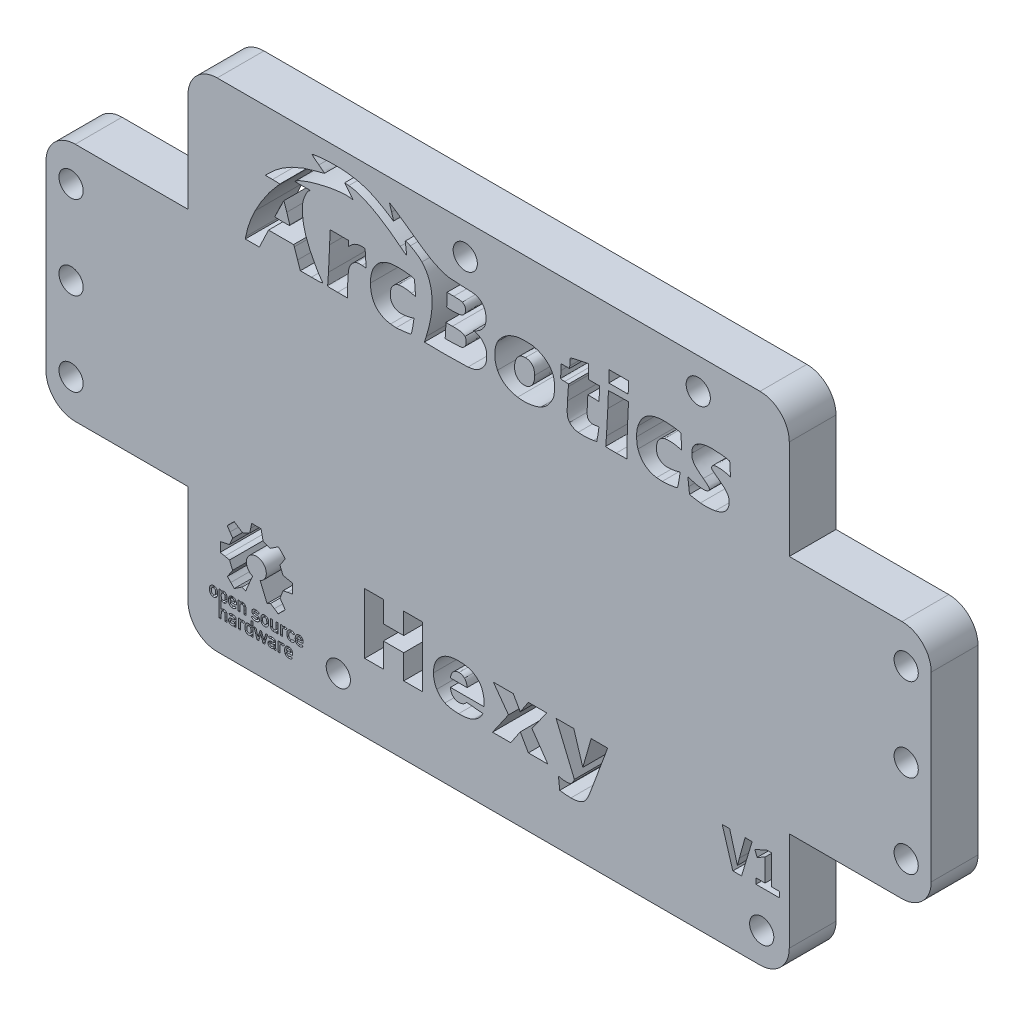
SolidWorks part; units mm, degrees
material "Acrylic (Medium-high impact)"
ref_plane "Front Plane" through (0, 0, 0) normal (0, 0, 1) x (1, 0, 0)
ref_plane "Top Plane" through (0, 0, 0) normal (0, 1, 0) x (1, 0, 0)
ref_plane "Right Plane" through (0, 0, 0) normal (1, 0, 0) x (0, 0, -1)
sketch "Model" plane through (0, 0, 0) normal (0, 0, 1) x (1, 0, 0)
  line L0 (572.6805, 435.5223) -> (572.6805, 426.8765) construction
  line L1 (569.4779, 431.9985) -> (569.8427, 432.8385)
  line L2 (571.0334, 434.0049) -> (571.8769, 434.371)
  line L3 (573.49, 434.3515) -> (574.3077, 434.03)
  line L4 (575.501, 432.879) -> (575.8699, 432.0026)
  line L5 (575.864, 430.3975) -> (575.5218, 429.4697)
  line L6 (569.4716, 430.3966) -> (569.8337, 429.5023)
  line L7 (577.0034, 431.7644) -> (577.0034, 430.6344)
  line L8 (613.0468, 464.5828) -> (613.4398, 464.6561)
  line L9 (613.4398, 464.6561) -> (613.5866, 465.4678)
  line L10 (612.3494, 468.6805) -> (612.3841, 468.9854)
  line L11 (612.3841, 468.9854) -> (613.0431, 468.9665)
  line L12 (613.0431, 468.9665) -> (613.702, 468.9476)
  line L13 (613.702, 468.9476) -> (613.7416, 469.5458)
  line L14 (613.7815, 470.3726) -> (613.7818, 470.6013)
  line L15 (613.7818, 470.6013) -> (613.104, 470.6013)
  line L16 (613.104, 470.6013) -> (612.4262, 470.6013)
  line L17 (612.4262, 470.6013) -> (612.4505, 471.4303)
  line L18 (612.4505, 471.4303) -> (612.4747, 472.2593)
  line L19 (612.4747, 472.2593) -> (612.2898, 472.2262)
  line L20 (610.2064, 470.8842) -> (610.1677, 470.6013)
  line L21 (610.1677, 470.6013) -> (609.6576, 470.6013)
  line L22 (609.6576, 470.6013) -> (609.1476, 470.6013)
  line L23 (609.1476, 470.6013) -> (609.1385, 469.8695)
  line L24 (609.5972, 468.9674) -> (610.0773, 468.9495)
  line L25 (610.0773, 468.9495) -> (610.0417, 468.6626)
  line L26 (629.2635, 469.038) -> (629.4705, 468.9537)
  line L27 (629.4705, 468.9537) -> (629.4316, 469.3659)
  line L28 (571.4078, 464.892) -> (571.358, 464.6256)
  line L29 (571.358, 464.6256) -> (572.2051, 464.6256)
  line L30 (636.4922, 464.2723) -> (653.4922, 464.2723)
  line L31 (572.2051, 464.6256) -> (573.0522, 464.6256)
  line L32 (573.0522, 464.6256) -> (573.1224, 464.7933)
  line L33 (573.6659, 465.9518) -> (574.1392, 466.9427)
  line L34 (574.1392, 466.9427) -> (575.6401, 466.9427)
  line L35 (575.6401, 466.9427) -> (577.1409, 466.9427)
  line L36 (577.1409, 466.9427) -> (577.2268, 466.7445)
  line L37 (577.6293, 465.586) -> (577.946, 464.6256)
  line L38 (577.946, 464.6256) -> (579.2783, 464.6256)
  line L39 (583.4807, 476.1434) -> (583.265, 476.411)
  line L40 (583.265, 476.411) -> (583.7519, 476.3661)
  line L41 (598.9104, 468.7408) -> (598.7037, 468.7854)
  line L42 (598.7037, 468.7854) -> (599.0698, 468.9611)
  line L43 (574.0883, 472.7703) -> (573.755, 472.4306)
  line L44 (573.755, 472.4306) -> (574.6219, 472.4306)
  line L45 (595.3267, 466.7695) -> (595.2871, 466.2609)
  line L46 (595.2871, 466.2609) -> (596.2569, 466.2817)
  line L47 (596.1632, 467.9793) -> (595.367, 467.9793)
  line L48 (595.367, 467.9793) -> (595.3666, 467.6287)
  line L49 (596.3182, 471.1699) -> (595.5194, 471.1805)
  line L50 (595.5194, 471.1805) -> (595.4882, 470.4183)
  line L51 (582.4095, 464.6256) -> (583.5985, 464.6256)
  line L52 (583.5985, 464.6256) -> (583.5996, 465.5555)
  line L53 (653.4922, 464.2723) -> (653.4922, 435.5223)
  line L54 (585.3449, 468.8801) -> (585.8119, 468.8501)
  line L55 (585.8119, 468.8501) -> (585.771, 469.7991)
  line L56 (583.9796, 470.2773) -> (583.7205, 470.0271)
  line L57 (583.7205, 470.0271) -> (583.7205, 470.3447)
  line L58 (583.7205, 470.3447) -> (583.7205, 470.6622)
  line L59 (583.7205, 470.6622) -> (582.6534, 470.6622)
  line L60 (615.7788, 464.6396) -> (617.0441, 464.6561)
  line L61 (617.0441, 464.6561) -> (617.0851, 466.9427)
  line L62 (617.2564, 470.5403) -> (617.2575, 470.6927)
  line L63 (617.2575, 470.6927) -> (616.061, 470.6801)
  line L64 (614.8794, 472.1562) -> (614.8794, 471.4549)
  line L65 (614.8794, 471.4549) -> (616.0297, 471.4549)
  line L66 (616.0297, 471.4549) -> (617.1799, 471.4549)
  line L67 (617.1799, 471.4549) -> (617.2187, 471.7378)
  line L68 (617.2575, 472.4391) -> (617.2575, 472.8574)
  line L69 (617.2575, 472.8574) -> (616.0685, 472.8574)
  line L70 (616.0685, 472.8574) -> (614.8794, 472.8574)
  line L71 (614.8794, 472.8574) -> (614.8794, 472.1562)
  line L72 (564.4922, 435.5223) -> (636.4922, 435.5223) construction
  line L73 (564.4922, 464.2723) -> (636.4922, 464.2723) construction
  line L74 (573.1347, 430.0968) -> (573.9653, 428.1256)
  line L75 (572.2263, 430.0968) -> (571.3958, 428.1256)
  line L76 (653.4922, 435.5223) -> (636.4922, 435.5223)
  line L77 (636.4922, 435.5223) -> (636.4922, 420.1473)
  line L78 (570.9723, 428.3321) -> (571.3958, 428.1256)
  line L79 (573.9653, 428.1256) -> (574.3746, 428.3252)
  line L80 (573.2198, 424.9354) -> (573.2198, 423.6854) construction
  line L81 (573.093, 424.1801) -> (573.2198, 424.5818)
  line L82 (573.2198, 424.5818) -> (573.3467, 424.1802)
  line L83 (568.3576, 431.7644) -> (568.3576, 430.6344)
  line L84 (568.3576, 431.1994) -> (577.0034, 431.1994) construction
  line L100 (636.4922, 420.1473) -> (564.4922, 420.1473)
  line L123 (564.4922, 420.1473) -> (564.4922, 435.5223)
  line L124 (564.4922, 435.5223) -> (547.4922, 435.5223)
  line L147 (547.4922, 435.5223) -> (547.4922, 464.2723)
  line L170 (547.4922, 464.2723) -> (564.4922, 464.2723)
  line L171 (564.4922, 464.2723) -> (564.4922, 479.6473)
  line L194 (564.4922, 479.6473) -> (636.4922, 479.6473)
  line L217 (636.4922, 479.6473) -> (636.4922, 464.2723)
  line L280 (585.6515, 435.5223) -> (587.8888, 435.5223)
  line L281 (587.8888, 435.5223) -> (587.8888, 432.9858)
  line L282 (587.8888, 432.9858) -> (590.3255, 432.9858)
  line L283 (590.3255, 432.9858) -> (590.3255, 435.5223)
  line L284 (590.3255, 435.5223) -> (592.5628, 435.5223)
  line L285 (592.5628, 435.5223) -> (592.5628, 428.2833)
  line L286 (592.5628, 428.2833) -> (590.3255, 428.2833)
  line L287 (590.3255, 428.2833) -> (590.3255, 431.2046)
  line L288 (590.3255, 431.2046) -> (587.8888, 431.2046)
  line L289 (587.8888, 431.2046) -> (587.8888, 428.2833)
  line L290 (587.8888, 428.2833) -> (585.6515, 428.2833)
  line L291 (585.6515, 428.2833) -> (585.6515, 435.5223)
  line L292 (599.9538, 430.4113) -> (595.921, 430.4113)
  line L293 (597.859, 429.8271) -> (599.8398, 429.6418)
  line L294 (599.9538, 430.6393) -> (599.9538, 430.4113)
  line L295 (595.921, 431.3803) -> (597.916, 431.3803)
  line L296 (601.0605, 433.5273) -> (603.4403, 433.5273)
  line L297 (603.4403, 433.5273) -> (604.281, 432.0596)
  line L298 (604.281, 432.0596) -> (605.25, 433.5273)
  line L299 (605.25, 433.5273) -> (607.4588, 433.5273)
  line L300 (607.4588, 433.5273) -> (605.6775, 431.0336)
  line L301 (605.6775, 431.0336) -> (607.587, 428.2833)
  line L302 (607.587, 428.2833) -> (605.25, 428.2833)
  line L303 (605.25, 428.2833) -> (604.281, 429.9791)
  line L304 (604.281, 429.9791) -> (603.141, 428.2833)
  line L305 (603.141, 428.2833) -> (600.9608, 428.2833)
  line L306 (600.9608, 428.2833) -> (602.8703, 431.0336)
  line L307 (602.8703, 431.0336) -> (601.0605, 433.5273)
  line L308 (608.5655, 433.5273) -> (610.6888, 433.5273)
  line L309 (610.6888, 433.5273) -> (611.7718, 430.0361)
  line L310 (611.7718, 430.0361) -> (612.7693, 433.5273)
  line L311 (612.7693, 433.5273) -> (614.75, 433.5273)
  line L312 (614.75, 433.5273) -> (612.6695, 427.9271)
  line L313 (609.0073, 426.2741) -> (608.8505, 427.6848)
  line L314 (610.76, 428.2833) -> (608.5655, 433.5273)
  line L315 (570.0018, 423.8327) -> (570.0506, 423.8801)
  line L316 (570.0506, 423.8801) -> (570.0506, 423.8256)
  line L317 (570.0506, 423.8256) -> (570.0506, 423.7711)
  line L318 (570.0506, 423.7711) -> (570.1612, 423.7711)
  line L319 (570.1612, 423.7711) -> (570.2717, 423.7711)
  line L320 (570.2717, 423.7711) -> (570.2716, 424.217)
  line L321 (569.4596, 424.8344) -> (569.3982, 424.7799)
  line L322 (569.3982, 424.7799) -> (569.4806, 424.7177)
  line L323 (570.0506, 424.5356) -> (570.0506, 424.4492)
  line L324 (570.0506, 424.4492) -> (569.8543, 424.4492)
  line L325 (570.0506, 424.1949) -> (570.0506, 424.2575)
  line L326 (570.0506, 424.2575) -> (569.8583, 424.2575)
  line L327 (571.9891, 423.8533) -> (572.0406, 423.8925)
  line L328 (572.0406, 423.8925) -> (572.0406, 423.8318)
  line L329 (572.0406, 423.8318) -> (572.0406, 423.7711)
  line L330 (572.0406, 423.7711) -> (572.1511, 423.7711)
  line L331 (572.1511, 423.7711) -> (572.2617, 423.7711)
  line L332 (572.2617, 423.7711) -> (572.2617, 424.5892)
  line L333 (572.2617, 424.5892) -> (572.2617, 425.4073)
  line L334 (572.2617, 425.4073) -> (572.1511, 425.4073)
  line L335 (572.1511, 425.4073) -> (572.0406, 425.4073)
  line L336 (572.0406, 425.4073) -> (572.0406, 425.1034)
  line L337 (572.0406, 425.1034) -> (572.0406, 424.7994)
  line L338 (572.0406, 424.7994) -> (571.9927, 424.8359)
  line L339 (574.7417, 423.841) -> (574.7822, 423.8798)
  line L340 (574.7822, 423.8798) -> (574.7822, 423.8255)
  line L341 (574.7822, 423.8255) -> (574.7822, 423.7711)
  line L342 (574.7822, 423.7711) -> (574.8936, 423.7711)
  line L343 (574.8936, 423.7711) -> (575.0049, 423.7711)
  line L344 (575.0049, 423.7711) -> (575.0004, 424.2329)
  line L345 (575.0004, 424.2329) -> (574.996, 424.6948)
  line L346 (574.996, 424.6948) -> (574.9512, 424.7671)
  line L347 (574.192, 424.8351) -> (574.1305, 424.7806)
  line L348 (574.1305, 424.7806) -> (574.2195, 424.7116)
  line L349 (574.7795, 424.5455) -> (574.7855, 424.4518)
  line L350 (574.7855, 424.4518) -> (574.5517, 424.4466)
  line L351 (574.7775, 424.1618) -> (574.7865, 424.2575)
  line L352 (574.7865, 424.2575) -> (574.589, 424.2575)
  line L353 (576.9334, 423.8826) -> (576.9939, 423.9373)
  line L354 (576.9939, 423.9373) -> (576.9323, 423.9905)
  line L355 (576.2959, 424.2023) -> (576.2876, 424.2575)
  line L356 (576.2876, 424.2575) -> (576.6552, 424.2575)
  line L357 (576.6552, 424.2575) -> (577.0227, 424.2575)
  line L358 (577.0227, 424.2575) -> (577.0227, 424.3797)
  line L359 (576.2941, 424.4897) -> (576.2852, 424.4492)
  line L360 (576.2852, 424.4492) -> (576.536, 424.4492)
  line L361 (576.536, 424.4492) -> (576.7869, 424.4492)
  line L362 (576.7869, 424.4492) -> (576.7866, 424.4971)
  line L363 (568.2376, 425.2746) -> (568.2376, 423.7711)
  line L364 (568.2376, 423.7711) -> (568.3555, 423.7711)
  line L365 (568.3555, 423.7711) -> (568.4734, 423.7711)
  line L366 (568.4734, 423.7711) -> (568.4734, 424.1558)
  line L367 (568.9423, 424.1581) -> (568.9469, 423.7711)
  line L368 (568.9469, 423.7711) -> (569.0574, 423.7711)
  line L369 (569.0574, 423.7711) -> (569.1678, 423.7711)
  line L370 (569.1678, 423.7711) -> (569.1633, 424.217)
  line L371 (568.514, 424.8425) -> (568.4734, 424.8043)
  line L372 (568.4734, 424.8043) -> (568.4734, 425.2697)
  line L373 (568.4734, 425.2697) -> (568.4734, 425.7351)
  line L374 (568.4734, 425.7351) -> (568.5268, 425.6944)
  line L375 (568.5479, 426.7123) -> (568.4734, 426.6622)
  line L376 (568.4734, 426.6622) -> (568.4734, 426.7201)
  line L377 (568.4734, 426.7201) -> (568.4734, 426.7781)
  line L378 (568.4734, 426.7781) -> (568.3555, 426.7781)
  line L379 (568.3555, 426.7781) -> (568.2376, 426.7781)
  line L380 (568.2376, 426.7781) -> (568.2376, 425.2746)
  line L381 (570.5371, 424.3534) -> (570.5371, 423.7711)
  line L382 (570.5371, 423.7711) -> (570.655, 423.7711)
  line L383 (570.655, 423.7711) -> (570.7729, 423.7711)
  line L384 (570.7729, 423.7711) -> (570.7729, 424.1581)
  line L385 (571.1047, 424.6913) -> (571.1605, 424.6648)
  line L386 (571.1605, 424.6648) -> (571.1959, 424.7081)
  line L387 (571.2747, 424.805) -> (571.3182, 424.8586)
  line L388 (571.3182, 424.8586) -> (571.2851, 424.8792)
  line L389 (570.8271, 424.8475) -> (570.7729, 424.7999)
  line L390 (570.7729, 424.7999) -> (570.7729, 424.8677)
  line L391 (570.7729, 424.8677) -> (570.7729, 424.9356)
  line L392 (570.7729, 424.9356) -> (570.655, 424.9356)
  line L393 (570.655, 424.9356) -> (570.5371, 424.9356)
  line L394 (570.5371, 424.9356) -> (570.5371, 424.3534)
  line L395 (572.6159, 424.2459) -> (572.7685, 423.7699)
  line L396 (572.7685, 423.7699) -> (572.8711, 423.7742)
  line L397 (572.8711, 423.7742) -> (572.9737, 423.7785)
  line L398 (572.9737, 423.7785) -> (573.093, 424.1801)
  line L399 (573.3467, 424.1802) -> (573.4658, 423.7785)
  line L400 (573.4658, 423.7785) -> (573.5697, 423.7742)
  line L401 (573.5697, 423.7742) -> (573.6737, 423.7699)
  line L402 (573.6737, 423.7699) -> (573.6969, 423.8479)
  line L403 (573.881, 424.4271) -> (574.042, 424.9282)
  line L404 (574.042, 424.9282) -> (573.9384, 424.9326)
  line L405 (573.4335, 424.5228) -> (573.3008, 424.9355)
  line L406 (573.3008, 424.9355) -> (573.2198, 424.9354)
  line L407 (573.2198, 424.9354) -> (573.1387, 424.9353)
  line L408 (573.1387, 424.9353) -> (573.0065, 424.5235)
  line L409 (572.7479, 424.5274) -> (572.6371, 424.9282)
  line L410 (572.6371, 424.9282) -> (572.5167, 424.9325)
  line L411 (572.5167, 424.9325) -> (572.3962, 424.9368)
  line L412 (572.3962, 424.9368) -> (572.4298, 424.8293)
  line L413 (575.2686, 424.3534) -> (575.2686, 423.7711)
  line L414 (575.2686, 423.7711) -> (575.3866, 423.7711)
  line L415 (575.3866, 423.7711) -> (575.5045, 423.7711)
  line L416 (575.5045, 423.7711) -> (575.5045, 424.1669)
  line L417 (575.9752, 424.7691) -> (576.0514, 424.8606)
  line L418 (576.0514, 424.8606) -> (575.9774, 424.8981)
  line L419 (575.5524, 424.8435) -> (575.5045, 424.7971)
  line L420 (575.5045, 424.7971) -> (575.5045, 424.8664)
  line L421 (575.5045, 424.8664) -> (575.5045, 424.9356)
  line L422 (575.5045, 424.9356) -> (575.3866, 424.9356)
  line L423 (575.3866, 424.9356) -> (575.2686, 424.9356)
  line L424 (575.2686, 424.9356) -> (575.2686, 424.3534)
  line L425 (569.5642, 426.0655) -> (569.5642, 426.1148)
  line L426 (569.5642, 426.1148) -> (569.9253, 426.1148)
  line L427 (569.9253, 426.1148) -> (570.2865, 426.1148)
  line L428 (570.2865, 426.1148) -> (570.2865, 426.2617)
  line L429 (569.5642, 426.3328) -> (569.5642, 426.2917)
  line L430 (569.5642, 426.2917) -> (569.8167, 426.2917)
  line L431 (569.8167, 426.2917) -> (570.0691, 426.2917)
  line L432 (570.0691, 426.2917) -> (570.0591, 426.3543)
  line L433 (572.8096, 426.5185) -> (572.8933, 426.4726)
  line L434 (572.8933, 426.4726) -> (572.9631, 426.5534)
  line L435 (572.9631, 426.5534) -> (573.033, 426.6343)
  line L436 (573.033, 426.6343) -> (572.9974, 426.662)
  line L437 (572.2902, 425.9108) -> (572.2282, 425.9557)
  line L438 (572.2282, 425.9557) -> (572.1546, 425.8821)
  line L439 (573.2126, 426.1956) -> (573.2124, 425.9594)
  line L440 (573.2124, 425.9594) -> (573.261, 425.8608)
  line L441 (575.0054, 425.6872) -> (575.0623, 425.733)
  line L442 (575.0623, 425.733) -> (575.0623, 425.6733)
  line L443 (575.0623, 425.6733) -> (575.0623, 425.6136)
  line L444 (575.0623, 425.6136) -> (575.1802, 425.6136)
  line L445 (575.1802, 425.6136) -> (575.2981, 425.6136)
  line L446 (575.2981, 425.6136) -> (575.2981, 426.1959)
  line L447 (575.2981, 426.1959) -> (575.2981, 426.7781)
  line L448 (575.2981, 426.7781) -> (575.1802, 426.7781)
  line L449 (575.1802, 426.7781) -> (575.0623, 426.7781)
  line L450 (575.0623, 426.7781) -> (575.0623, 426.3868)
  line L451 (574.5906, 426.4324) -> (574.5906, 426.7781)
  line L452 (574.5906, 426.7781) -> (574.4793, 426.7781)
  line L453 (574.4793, 426.7781) -> (574.3679, 426.7781)
  line L454 (574.3679, 426.7781) -> (574.3724, 426.3322)
  line L455 (574.3724, 426.3322) -> (574.3769, 425.8863)
  line L456 (574.3769, 425.8863) -> (574.4223, 425.8053)
  line L457 (577.1983, 425.7395) -> (577.2598, 425.795)
  line L458 (577.2598, 425.795) -> (577.2186, 425.8383)
  line L459 (577.2186, 426.5534) -> (577.2598, 426.5967)
  line L460 (577.2598, 426.5967) -> (577.1983, 426.6523)
  line L461 (578.2083, 425.7326) -> (578.2649, 425.7823)
  line L462 (578.2649, 425.7823) -> (578.1856, 425.8522)
  line L463 (577.5714, 426.0417) -> (577.5644, 426.1148)
  line L464 (577.5644, 426.1148) -> (577.92, 426.1148)
  line L465 (577.92, 426.1148) -> (578.2756, 426.1148)
  line L466 (578.2756, 426.1148) -> (578.2755, 426.2806)
  line L467 (577.5681, 426.341) -> (577.5681, 426.2917)
  line L468 (577.5681, 426.2917) -> (577.8183, 426.2917)
  line L469 (577.8183, 426.2917) -> (578.0685, 426.2917)
  line L470 (578.0685, 426.2917) -> (578.0602, 426.3396)
  line L471 (570.5076, 426.1959) -> (570.5076, 425.6136)
  line L472 (570.5076, 425.6136) -> (570.6181, 425.6136)
  line L473 (570.6181, 425.6136) -> (570.7287, 425.6136)
  line L474 (570.7287, 425.6136) -> (570.729, 425.9932)
  line L475 (571.2, 425.9932) -> (571.2004, 425.6136)
  line L476 (571.2004, 425.6136) -> (571.3109, 425.6136)
  line L477 (571.3109, 425.6136) -> (571.4215, 425.6136)
  line L478 (571.4215, 425.6136) -> (571.4213, 426.0522)
  line L479 (570.7766, 426.6851) -> (570.7287, 426.6397)
  line L480 (570.7287, 426.6397) -> (570.7287, 426.7089)
  line L481 (570.7287, 426.7089) -> (570.7287, 426.7781)
  line L482 (570.7287, 426.7781) -> (570.6181, 426.7781)
  line L483 (570.6181, 426.7781) -> (570.5076, 426.7781)
  line L484 (570.5076, 426.7781) -> (570.5076, 426.1959)
  line L485 (575.7872, 426.0079) -> (575.7824, 425.6136)
  line L486 (575.7824, 425.6136) -> (575.6729, 425.6136)
  line L487 (575.6729, 425.6136) -> (575.5635, 425.6136)
  line L488 (575.5635, 425.6136) -> (575.5635, 426.1959)
  line L489 (575.5635, 426.1959) -> (575.5635, 426.7781)
  line L490 (575.5635, 426.7781) -> (575.674, 426.7781)
  line L491 (575.674, 426.7781) -> (575.7846, 426.7781)
  line L492 (575.7846, 426.7781) -> (575.7846, 426.7192)
  line L493 (573.2459, 435.5223) -> (572.1151, 435.5223)
  line L497 (600.4922, -493.6423) -> (600.4922, 47006.3577) construction
  line L498 (-451.9635, 449.8973) -> (49548.0365, 449.8973) construction
  circle A0 centre (550.4922, 449.8973) radius 1.45
  circle A1 centre (550.4922, 459.8973) radius 1.45
  circle A2 centre (550.4922, 439.8973) radius 1.45
  circle A3 centre (650.4922, 439.8973) radius 1.45
  circle A4 centre (650.4922, 459.8973) radius 1.45
  circle A5 centre (650.4922, 449.8973) radius 1.45
  circle A6 centre (597.6922, 475.9473) radius 1.45
  circle A7 centre (625.5922, 475.9473) radius 1.45
  circle A8 centre (633.1922, 423.8473) radius 1.45
  circle A9 centre (582.4922, 425.1473) radius 1.45
  arc A10 (572.2263, 430.0968) -> (573.1347, 430.0968) centre (572.6805, 431.1994) cw
  circle A11 centre (572.6805, 431.1994) radius 4.3229 construction
  circle A12 centre (572.6805, 431.1994) radius 3.2299 construction
  spline S0 degree 3 poles (588.751, 464.5107) (588.9523, 464.4814) (589.2541, 464.4547) (589.4218, 464.4513) knots 0 0 0 0 1 1 1 1
  spline S1 degree 3 poles (589.4218, 464.4513) (589.7218, 464.4451) (590.9484, 464.589) (591.155, 464.6546) knots 0 0 0 0 1 1 1 1
  spline S2 degree 3 poles (591.155, 464.6546) (591.2389, 464.6812) (591.2926, 464.8736) (591.4151, 465.5868) knots 0 0 0 0 1 1 1 1
  spline S3 degree 3 poles (591.4151, 465.5868) (591.5, 466.081) (591.5652, 466.4911) (591.5601, 466.4981) knots 0 0 0 0 1 1 1 1
  spline S4 degree 3 poles (591.5601, 466.4981) (591.5549, 466.5052) (591.3821, 466.4584) (591.1761, 466.3943) knots 0 0 0 0 1 1 1 1
  spline S5 degree 3 poles (591.1761, 466.3943) (590.6782, 466.2394) (589.976, 466.1795) (589.6597, 466.2651) knots 0 0 0 0 1 1 1 1
  spline S6 degree 3 poles (589.6597, 466.2651) (589.0365, 466.4336) (588.7206, 466.8674) (588.7206, 467.5545) knots 0 0 0 0 1 1 1 1
  spline S7 degree 3 poles (588.7206, 467.5545) (588.7206, 467.7762) (588.7639, 468.0847) (588.8168, 468.24) knots 0 0 0 0 1 1 1 1
  spline S8 degree 3 poles (588.8168, 468.24) (588.936, 468.59) (589.2906, 468.9229) (589.647, 469.0196) knots 0 0 0 0 1 1 1 1
  spline S9 degree 3 poles (589.647, 469.0196) (590.0322, 469.1241) (590.6962, 469.098) (591.2459, 468.9568) knots 0 0 0 0 1 1 1 1
  spline S10 degree 3 poles (591.2459, 468.9568) (591.5114, 468.8886) (591.7328, 468.8397) (591.738, 468.8481) knots 0 0 0 0 1 1 1 1
  spline S11 degree 3 poles (591.738, 468.8481) (591.7579, 468.8806) (591.6354, 470.5721) (591.6114, 470.5964) knots 0 0 0 0 1 1 1 1
  spline S12 degree 3 poles (591.6114, 470.5964) (591.5974, 470.6105) (591.4146, 470.6594) (591.2051, 470.7051) knots 0 0 0 0 1 1 1 1
  spline S13 degree 3 poles (591.2051, 470.7051) (590.6128, 470.8343) (589.4589, 470.8749) (588.8692, 470.7871) knots 0 0 0 0 1 1 1 1
  spline S14 degree 3 poles (588.8692, 470.7871) (587.2787, 470.5505) (586.3406, 469.3476) (586.3434, 467.5485) knots 0 0 0 0 1 1 1 1
  spline S15 degree 3 poles (586.3434, 467.5485) (586.3461, 465.8019) (587.1897, 464.7374) (588.751, 464.5107) knots 0 0 0 0 1 1 1 1
  spline S16 degree 3 poles (603.9646, 464.5298) (604.8317, 464.3732) (606.0481, 464.5344) (606.7739, 464.9022) knots 0 0 0 0 1 1 1 1
  spline S17 degree 3 poles (606.7739, 464.9022) (607.4037, 465.2213) (607.9804, 465.8932) (608.2417, 466.6122) knots 0 0 0 0 1 1 1 1
  spline S18 degree 3 poles (608.2417, 466.6122) (608.4308, 467.1328) (608.4339, 468.3414) (608.2473, 468.8472) knots 0 0 0 0 1 1 1 1
  spline S19 degree 3 poles (608.2473, 468.8472) (607.9277, 469.7135) (607.2666, 470.3089) (606.2513, 470.6451) knots 0 0 0 0 1 1 1 1
  spline S20 degree 3 poles (606.2513, 470.6451) (605.8244, 470.7864) (605.6606, 470.8071) (604.9403, 470.8106) knots 0 0 0 0 1 1 1 1
  spline S21 degree 3 poles (604.9403, 470.8106) (604.0301, 470.8151) (603.5723, 470.7134) (602.8408, 470.3441) knots 0 0 0 0 1 1 1 1
  spline S22 degree 3 poles (602.8408, 470.3441) (602.3905, 470.1168) (601.7794, 469.5175) (601.5635, 469.0915) knots 0 0 0 0 1 1 1 1
  spline S23 degree 3 poles (601.5635, 469.0915) (601.1143, 468.2051) (601.1113, 467.0357) (601.5559, 466.1176) knots 0 0 0 0 1 1 1 1
  spline S24 degree 3 poles (601.5559, 466.1176) (601.9593, 465.2845) (602.7792, 464.744) (603.9646, 464.5298) knots 0 0 0 0 1 1 1 1
  spline S25 degree 3 poles (603.6624, 466.9903) (603.8399, 466.3513) (604.5661, 465.9923) (605.1709, 466.2445) knots 0 0 0 0 1 1 1 1
  spline S26 degree 3 poles (605.1709, 466.2445) (605.7256, 466.4759) (606.0076, 467.0019) (606.0029, 467.7963) knots 0 0 0 0 1 1 1 1
  spline S27 degree 3 poles (606.0029, 467.7963) (605.9979, 468.6361) (605.6122, 469.0856) (604.8956, 469.0866) knots 0 0 0 0 1 1 1 1
  spline S28 degree 3 poles (604.8956, 469.0866) (604.5085, 469.0872) (604.2405, 468.9745) (604.0026, 468.7112) knots 0 0 0 0 1 1 1 1
  spline S29 degree 3 poles (604.0026, 468.7112) (603.6511, 468.3222) (603.502, 467.5679) (603.6624, 466.9903) knots 0 0 0 0 1 1 1 1
  spline S30 degree 3 poles (613.5866, 465.4678) (613.6674, 465.9143) (613.7199, 466.2933) (613.7032, 466.31) knots 0 0 0 0 1 1 1 1
  spline S31 degree 3 poles (613.7032, 466.31) (613.6864, 466.3267) (613.5083, 466.3064) (613.3073, 466.2649) knots 0 0 0 0 1 1 1 1
  spline S32 degree 3 poles (613.3073, 466.2649) (612.8597, 466.1724) (612.5951, 466.235) (612.4161, 466.4758) knots 0 0 0 0 1 1 1 1
  spline S33 degree 3 poles (612.4161, 466.4758) (612.2983, 466.6342) (612.289, 466.7178) (612.3013, 467.5119) knots 0 0 0 0 1 1 1 1
  spline S34 degree 3 poles (612.3013, 467.5119) (612.3086, 467.9869) (612.3302, 468.5128) (612.3494, 468.6805) knots 0 0 0 0 1 1 1 1
  spline S35 degree 3 poles (613.7416, 469.5458) (613.7634, 469.8748) (613.7814, 470.2468) (613.7815, 470.3726) knots 0 0 0 0 1 1 1 1
  spline S36 degree 3 poles (612.2898, 472.2262) (611.9814, 472.1711) (610.403, 471.8233) (610.3214, 471.7924) knots 0 0 0 0 1 1 1 1
  spline S37 degree 3 poles (610.3214, 471.7924) (610.2748, 471.7748) (610.2452, 471.648) (610.2452, 471.4654) knots 0 0 0 0 1 1 1 1
  spline S38 degree 3 poles (610.2452, 471.4654) (610.2452, 471.3013) (610.2278, 471.0398) (610.2064, 470.8842) knots 0 0 0 0 1 1 1 1
  spline S39 degree 3 poles (609.1385, 469.8695) (609.1335, 469.4671) (609.1266, 469.1035) (609.1232, 469.0616) knots 0 0 0 0 1 1 1 1
  spline S40 degree 3 poles (609.1232, 469.0616) (609.119, 469.0079) (609.2592, 468.9801) (609.5972, 468.9674) knots 0 0 0 0 1 1 1 1
  spline S41 degree 3 poles (610.0417, 468.6626) (610.0221, 468.5047) (609.9737, 467.818) (609.934, 467.1365) knots 0 0 0 0 1 1 1 1
  spline S42 degree 3 poles (609.934, 467.1365) (609.8511, 465.7111) (609.8893, 465.399) (610.1919, 465.0319) knots 0 0 0 0 1 1 1 1
  spline S43 degree 3 poles (610.1919, 465.0319) (610.4256, 464.7483) (610.7584, 464.5756) (611.2081, 464.5046) knots 0 0 0 0 1 1 1 1
  spline S44 degree 3 poles (611.2081, 464.5046) (611.6129, 464.4406) (612.483, 464.4776) (613.0468, 464.5828) knots 0 0 0 0 1 1 1 1
  spline S45 degree 3 poles (620.6082, 464.5073) (620.7943, 464.4799) (621.0975, 464.4547) (621.2819, 464.4513) knots 0 0 0 0 1 1 1 1
  spline S46 degree 3 poles (621.2819, 464.4513) (621.6977, 464.4435) (622.8842, 464.5977) (623.0366, 464.6792) knots 0 0 0 0 1 1 1 1
  spline S47 degree 3 poles (623.0366, 464.6792) (623.1253, 464.7267) (623.1777, 464.912) (623.2835, 465.5515) knots 0 0 0 0 1 1 1 1
  spline S48 degree 3 poles (623.2835, 465.5515) (623.3573, 465.998) (623.4173, 466.3965) (623.4169, 466.4369) knots 0 0 0 0 1 1 1 1
  spline S49 degree 3 poles (623.4169, 466.4369) (623.4163, 466.492) (623.3538, 466.4885) (623.1676, 466.4228) knots 0 0 0 0 1 1 1 1
  spline S50 degree 3 poles (623.1676, 466.4228) (622.6866, 466.253) (621.9405, 466.1806) (621.5569, 466.2665) knots 0 0 0 0 1 1 1 1
  spline S51 degree 3 poles (621.5569, 466.2665) (621.1463, 466.3584) (620.7771, 466.6551) (620.6702, 466.9792) knots 0 0 0 0 1 1 1 1
  spline S52 degree 3 poles (620.6702, 466.9792) (620.5588, 467.3166) (620.5831, 467.9896) (620.7176, 468.2937) knots 0 0 0 0 1 1 1 1
  spline S53 degree 3 poles (620.7176, 468.2937) (620.8662, 468.6296) (621.206, 468.9296) (621.5403, 469.0202) knots 0 0 0 0 1 1 1 1
  spline S54 degree 3 poles (621.5403, 469.0202) (622.0074, 469.1466) (622.9549, 469.0685) (623.4985, 468.8587) knots 0 0 0 0 1 1 1 1
  spline S55 degree 3 poles (623.4985, 468.8587) (623.6063, 468.8171) (623.6093, 468.8543) (623.5673, 469.693) knots 0 0 0 0 1 1 1 1
  spline S56 degree 3 poles (623.5673, 469.693) (623.543, 470.1758) (623.5143, 470.5807) (623.5034, 470.5929) knots 0 0 0 0 1 1 1 1
  spline S57 degree 3 poles (623.5034, 470.5929) (623.4391, 470.6649) (622.6091, 470.7901) (621.9722, 470.8239) knots 0 0 0 0 1 1 1 1
  spline S58 degree 3 poles (621.9722, 470.8239) (619.973, 470.93) (618.8783, 470.2985) (618.3793, 468.7511) knots 0 0 0 0 1 1 1 1
  spline S59 degree 3 poles (618.3793, 468.7511) (618.2448, 468.3338) (618.2187, 468.1407) (618.2176, 467.5524) knots 0 0 0 0 1 1 1 1
  spline S60 degree 3 poles (618.2176, 467.5524) (618.2166, 466.9559) (618.2404, 466.7784) (618.3775, 466.3634) knots 0 0 0 0 1 1 1 1
  spline S61 degree 3 poles (618.3775, 466.3634) (618.7209, 465.324) (619.5077, 464.6694) (620.6082, 464.5073) knots 0 0 0 0 1 1 1 1
  spline S62 degree 3 poles (629.4316, 469.3659) (629.4102, 469.5926) (629.392, 469.9427) (629.3913, 470.1439) knots 0 0 0 0 1 1 1 1
  spline S63 degree 3 poles (629.3913, 470.1439) (629.3905, 470.3452) (629.3687, 470.5433) (629.3427, 470.5841) knots 0 0 0 0 1 1 1 1
  spline S64 degree 3 poles (629.3427, 470.5841) (629.3153, 470.6273) (628.9509, 470.7006) (628.4747, 470.7589) knots 0 0 0 0 1 1 1 1
  spline S65 degree 3 poles (628.4747, 470.7589) (626.0624, 471.0538) (624.8186, 470.5008) (624.8186, 469.1333) knots 0 0 0 0 1 1 1 1
  spline S66 degree 3 poles (624.8186, 469.1333) (624.8186, 468.4033) (625.0689, 468.054) (626.1985, 467.2082) knots 0 0 0 0 1 1 1 1
  spline S67 degree 3 poles (626.1985, 467.2082) (626.9069, 466.6777) (627.0148, 466.5282) (626.8597, 466.2914) knots 0 0 0 0 1 1 1 1
  spline S68 degree 3 poles (626.8597, 466.2914) (626.6739, 466.0079) (625.7177, 466.0195) (624.865, 466.3157) knots 0 0 0 0 1 1 1 1
  spline S69 degree 3 poles (624.865, 466.3157) (624.3442, 466.4967) (624.3328, 466.4979) (624.3589, 466.3711) knots 0 0 0 0 1 1 1 1
  spline S70 degree 3 poles (624.3589, 466.3711) (624.3737, 466.2998) (624.4171, 465.9122) (624.4556, 465.5097) knots 0 0 0 0 1 1 1 1
  spline S71 degree 3 poles (624.4556, 465.5097) (624.494, 465.1073) (624.5357, 464.7615) (624.5481, 464.7412) knots 0 0 0 0 1 1 1 1
  spline S72 degree 3 poles (624.5481, 464.7412) (624.5714, 464.7035) (625.1522, 464.5978) (625.8552, 464.5033) knots 0 0 0 0 1 1 1 1
  spline S73 degree 3 poles (625.8552, 464.5033) (626.324, 464.4403) (627.1683, 464.4727) (627.6278, 464.5712) knots 0 0 0 0 1 1 1 1
  spline S74 degree 3 poles (627.6278, 464.5712) (628.706, 464.8025) (629.2952, 465.4034) (629.2947, 466.2714) knots 0 0 0 0 1 1 1 1
  spline S75 degree 3 poles (629.2947, 466.2714) (629.2944, 466.9723) (629.0041, 467.3611) (627.8797, 468.1664) knots 0 0 0 0 1 1 1 1
  spline S76 degree 3 poles (627.8797, 468.1664) (627.5879, 468.3754) (627.3148, 468.5887) (627.2729, 468.6404) knots 0 0 0 0 1 1 1 1
  spline S77 degree 3 poles (627.2729, 468.6404) (627.1611, 468.7781) (627.1798, 468.9818) (627.3156, 469.1047) knots 0 0 0 0 1 1 1 1
  spline S78 degree 3 poles (627.3156, 469.1047) (627.5551, 469.3214) (628.6601, 469.2835) (629.2635, 469.038) knots 0 0 0 0 1 1 1 1
  spline S79 degree 3 poles (573.1224, 464.7933) (573.161, 464.8855) (573.4056, 465.4068) (573.6659, 465.9518) knots 0 0 0 0 1 1 1 1
  spline S80 degree 3 poles (577.2268, 466.7445) (577.274, 466.6355) (577.4551, 466.1142) (577.6293, 465.586) knots 0 0 0 0 1 1 1 1
  spline S81 degree 3 poles (579.2783, 464.6256) (580.735, 464.6256) (580.7483, 464.6294) (580.4612, 464.9635) knots 0 0 0 0 1 1 1 1
  spline S82 degree 3 poles (580.4612, 464.9635) (580.2053, 465.2614) (579.4153, 466.6377) (579.1153, 467.3085) knots 0 0 0 0 1 1 1 1
  spline S83 degree 3 poles (579.1153, 467.3085) (578.4572, 468.7799) (578.2157, 469.7455) (578.2078, 470.9366) knots 0 0 0 0 1 1 1 1
  spline S84 degree 3 poles (578.2078, 470.9366) (578.2029, 471.6707) (578.2221, 471.8544) (578.3448, 472.2476) knots 0 0 0 0 1 1 1 1
  spline S85 degree 3 poles (578.3448, 472.2476) (578.5066, 472.7668) (578.7996, 473.3175) (578.9708, 473.4244) knots 0 0 0 0 1 1 1 1
  spline S86 degree 3 poles (578.9708, 473.4244) (579.0343, 473.464) (579.0863, 473.5152) (579.0863, 473.5381) knots 0 0 0 0 1 1 1 1
  spline S87 degree 3 poles (579.0863, 473.5381) (579.0863, 473.5611) (578.6678, 473.5683) (578.1564, 473.5544) knots 0 0 0 0 1 1 1 1
  spline S88 degree 3 poles (578.1564, 473.5544) (577.3019, 473.531) (577.2364, 473.5367) (577.3485, 473.6249) knots 0 0 0 0 1 1 1 1
  spline S89 degree 3 poles (577.3485, 473.6249) (578.3291, 474.397) (582.5556, 475.4107) (583.846, 475.1834) knots 0 0 0 0 1 1 1 1
  spline S90 degree 3 poles (583.846, 475.1834) (584.0576, 475.1461) (584.2404, 475.1252) (584.2521, 475.137) knots 0 0 0 0 1 1 1 1
  spline S91 degree 3 poles (584.2521, 475.137) (584.2638, 475.1487) (584.1435, 475.3197) (583.9848, 475.517) knots 0 0 0 0 1 1 1 1
  spline S92 degree 3 poles (583.9848, 475.517) (583.8261, 475.7143) (583.5993, 475.9962) (583.4807, 476.1434) knots 0 0 0 0 1 1 1 1
  spline S93 degree 3 poles (583.7519, 476.3661) (585.2991, 476.2234) (587.5711, 475.0303) (589.9032, 473.1357) knots 0 0 0 0 1 1 1 1
  spline S94 degree 3 poles (589.9032, 473.1357) (590.3011, 472.8124) (590.6389, 472.5603) (590.654, 472.5753) knots 0 0 0 0 1 1 1 1
  spline S95 degree 3 poles (590.654, 472.5753) (590.6834, 472.6048) (590.5632, 473.7333) (590.5118, 473.9092) knots 0 0 0 0 1 1 1 1
  spline S96 degree 3 poles (590.5118, 473.9092) (590.4642, 474.0722) (590.6219, 474.0424) (591.1154, 473.7954) knots 0 0 0 0 1 1 1 1
  spline S97 degree 3 poles (591.1154, 473.7954) (591.6484, 473.5286) (592.2098, 473.1344) (592.5084, 472.8174) knots 0 0 0 0 1 1 1 1
  spline S98 degree 3 poles (592.5084, 472.8174) (593.9305, 471.3076) (594.1089, 468.6937) (593.0182, 465.3464) knots 0 0 0 0 1 1 1 1
  spline S99 degree 3 poles (593.0182, 465.3464) (592.9015, 464.9882) (592.806, 464.6795) (592.806, 464.6604) knots 0 0 0 0 1 1 1 1
  spline S100 degree 3 poles (592.806, 464.6604) (592.806, 464.6041) (597.4191, 464.6238) (598.0195, 464.6827) knots 0 0 0 0 1 1 1 1
  spline S101 degree 3 poles (598.0195, 464.6827) (598.7932, 464.7585) (599.2138, 464.9319) (599.6387, 465.3505) knots 0 0 0 0 1 1 1 1
  spline S102 degree 3 poles (599.6387, 465.3505) (600.0908, 465.7959) (600.2617, 466.2221) (600.2649, 466.9122) knots 0 0 0 0 1 1 1 1
  spline S103 degree 3 poles (600.2649, 466.9122) (600.2675, 467.4847) (600.1436, 467.8213) (599.7836, 468.2198) knots 0 0 0 0 1 1 1 1
  spline S104 degree 3 poles (599.7836, 468.2198) (599.5356, 468.4942) (599.2427, 468.669) (598.9104, 468.7408) knots 0 0 0 0 1 1 1 1
  spline S105 degree 3 poles (599.0698, 468.9611) (599.5315, 469.1827) (599.885, 469.5633) (600.0598, 470.0269) knots 0 0 0 0 1 1 1 1
  spline S106 degree 3 poles (600.0598, 470.0269) (600.2586, 470.5544) (600.2194, 471.3052) (599.9674, 471.7956) knots 0 0 0 0 1 1 1 1
  spline S107 degree 3 poles (599.9674, 471.7956) (599.7745, 472.1709) (599.3965, 472.4857) (598.9757, 472.6215) knots 0 0 0 0 1 1 1 1
  spline S108 degree 3 poles (598.9757, 472.6215) (598.8459, 472.6634) (598.1338, 472.711) (597.2877, 472.7343) knots 0 0 0 0 1 1 1 1
  spline S109 degree 3 poles (597.2877, 472.7343) (595.6821, 472.7786) (595.5355, 472.8052) (594.4218, 473.2547) knots 0 0 0 0 1 1 1 1
  spline S110 degree 3 poles (594.4218, 473.2547) (593.5737, 473.597) (593.0855, 473.9093) (590.6325, 475.6784) knots 0 0 0 0 1 1 1 1
  spline S111 degree 3 poles (590.6325, 475.6784) (589.6106, 476.4154) (588.6696, 477.0359) (588.6341, 476.9962) knots 0 0 0 0 1 1 1 1
  spline S112 degree 3 poles (588.6341, 476.9962) (588.6228, 476.9836) (588.7313, 476.6166) (588.8752, 476.1806) knots 0 0 0 0 1 1 1 1
  spline S113 degree 3 poles (588.8752, 476.1806) (589.0191, 475.7446) (589.1251, 475.376) (589.1107, 475.3615) knots 0 0 0 0 1 1 1 1
  spline S114 degree 3 poles (589.1107, 475.3615) (589.0962, 475.347) (589.0094, 475.3944) (588.9177, 475.467) knots 0 0 0 0 1 1 1 1
  spline S115 degree 3 poles (588.9177, 475.467) (588.5803, 475.734) (587.4253, 476.4083) (586.7564, 476.7288) knots 0 0 0 0 1 1 1 1
  spline S116 degree 3 poles (586.7564, 476.7288) (585.2711, 477.4404) (583.6743, 477.7262) (581.5863, 477.6542) knots 0 0 0 0 1 1 1 1
  spline S117 degree 3 poles (581.5863, 477.6542) (580.6299, 477.6212) (580.0011, 477.5614) (579.495, 477.4554) knots 0 0 0 0 1 1 1 1
  spline S118 degree 3 poles (579.495, 477.4554) (579.3478, 477.4246) (579.3353, 477.4063) (579.4035, 477.3229) knots 0 0 0 0 1 1 1 1
  spline S119 degree 3 poles (579.4035, 477.3229) (579.447, 477.2697) (579.7937, 476.9956) (580.1739, 476.7138) knots 0 0 0 0 1 1 1 1
  spline S120 degree 3 poles (580.1739, 476.7138) (580.5541, 476.4319) (580.8517, 476.1879) (580.8352, 476.1713) knots 0 0 0 0 1 1 1 1
  spline S121 degree 3 poles (580.8352, 476.1713) (580.8187, 476.1548) (580.4253, 476.0491) (579.961, 475.9364) knots 0 0 0 0 1 1 1 1
  spline S122 degree 3 poles (579.961, 475.9364) (577.4488, 475.3267) (575.6386, 474.3508) (574.0883, 472.7703) knots 0 0 0 0 1 1 1 1
  spline S123 degree 3 poles (574.6219, 472.4306) (575.0986, 472.4306) (575.4887, 472.4135) (575.4887, 472.3926) knots 0 0 0 0 1 1 1 1
  spline S124 degree 3 poles (575.4887, 472.3926) (575.4887, 472.3717) (575.3309, 472.1854) (575.1381, 471.9786) knots 0 0 0 0 1 1 1 1
  spline S125 degree 3 poles (575.1381, 471.9786) (574.2689, 471.0463) (573.1298, 469.3688) (572.5322, 468.141) knots 0 0 0 0 1 1 1 1
  spline S126 degree 3 poles (572.5322, 468.141) (571.9534, 466.9517) (571.604, 465.9422) (571.4078, 464.892) knots 0 0 0 0 1 1 1 1
  spline S127 degree 3 poles (596.2569, 466.2817) (597.0882, 466.2995) (597.2549, 466.3195) (597.4239, 466.4217) knots 0 0 0 0 1 1 1 1
  spline S128 degree 3 poles (597.4239, 466.4217) (597.8189, 466.6606) (597.9416, 467.321) (597.6544, 467.6623) knots 0 0 0 0 1 1 1 1
  spline S129 degree 3 poles (597.6544, 467.6623) (597.4469, 467.9089) (597.1159, 467.9793) (596.1632, 467.9793) knots 0 0 0 0 1 1 1 1
  spline S130 degree 3 poles (595.3666, 467.6287) (595.3664, 467.4358) (595.3484, 467.0492) (595.3267, 466.7695) knots 0 0 0 0 1 1 1 1
  spline S131 degree 3 poles (576.6801, 468.7567) (576.7182, 468.658) (576.6522, 468.65) (575.795, 468.65) knots 0 0 0 0 1 1 1 1
  spline S132 degree 3 poles (575.795, 468.65) (575.2856, 468.65) (574.8779, 468.6736) (574.8891, 468.7024) knots 0 0 0 0 1 1 1 1
  spline S133 degree 3 poles (574.8891, 468.7024) (574.9863, 468.9529) (575.948, 470.9059) (575.9736, 470.9049) knots 0 0 0 0 1 1 1 1
  spline S134 degree 3 poles (575.9736, 470.9049) (575.992, 470.9042) (576.1492, 470.4446) (576.323, 469.8835) knots 0 0 0 0 1 1 1 1
  spline S135 degree 3 poles (576.323, 469.8835) (576.4967, 469.3225) (576.6574, 468.8154) (576.6801, 468.7567) knots 0 0 0 0 1 1 1 1
  spline S136 degree 3 poles (595.4882, 470.4183) (595.471, 469.9991) (595.4679, 469.6321) (595.4813, 469.6027) knots 0 0 0 0 1 1 1 1
  spline S137 degree 3 poles (595.4813, 469.6027) (595.4947, 469.5733) (595.8654, 469.5618) (596.3052, 469.5771) knots 0 0 0 0 1 1 1 1
  spline S138 degree 3 poles (596.3052, 469.5771) (596.8946, 469.5976) (597.1567, 469.6321) (597.3024, 469.708) knots 0 0 0 0 1 1 1 1
  spline S139 degree 3 poles (597.3024, 469.708) (597.8642, 470.0011) (597.8846, 470.8386) (597.3355, 471.068) knots 0 0 0 0 1 1 1 1
  spline S140 degree 3 poles (597.3355, 471.068) (597.1849, 471.1309) (596.8686, 471.1626) (596.3182, 471.1699) knots 0 0 0 0 1 1 1 1
  spline S141 degree 3 poles (583.5996, 465.5555) (583.6008, 466.6301) (583.6819, 467.5231) (583.8147, 467.925) knots 0 0 0 0 1 1 1 1
  spline S142 degree 3 poles (583.8147, 467.925) (583.9421, 468.3107) (584.2723, 468.6788) (584.6047, 468.8057) knots 0 0 0 0 1 1 1 1
  spline S143 degree 3 poles (584.6047, 468.8057) (584.81, 468.8841) (584.9939, 468.9026) (585.3449, 468.8801) knots 0 0 0 0 1 1 1 1
  spline S144 degree 3 poles (585.771, 469.7991) (585.7433, 470.4398) (585.7057, 470.7649) (585.6552, 470.7998) knots 0 0 0 0 1 1 1 1
  spline S145 degree 3 poles (585.6552, 470.7998) (585.614, 470.8283) (585.4019, 470.8405) (585.1839, 470.827) knots 0 0 0 0 1 1 1 1
  spline S146 degree 3 poles (585.1839, 470.827) (584.7111, 470.7977) (584.346, 470.6311) (583.9796, 470.2773) knots 0 0 0 0 1 1 1 1
  spline S147 degree 3 poles (582.6534, 470.6622) (582.0665, 470.6622) (581.5657, 470.6691) (581.5406, 470.6775) knots 0 0 0 0 1 1 1 1
  spline S148 degree 3 poles (581.5406, 470.6775) (581.5154, 470.6859) (581.4763, 469.9656) (581.4536, 469.0769) knots 0 0 0 0 1 1 1 1
  spline S149 degree 3 poles (581.4536, 469.0769) (581.431, 468.1881) (581.3692, 466.8737) (581.3164, 466.156) knots 0 0 0 0 1 1 1 1
  spline S150 degree 3 poles (581.3164, 466.156) (581.2636, 465.4382) (581.2205, 464.8003) (581.2205, 464.7383) knots 0 0 0 0 1 1 1 1
  spline S151 degree 3 poles (581.2205, 464.7383) (581.2205, 464.6325) (581.2936, 464.6256) (582.4095, 464.6256) knots 0 0 0 0 1 1 1 1
  spline S152 degree 3 poles (617.0851, 466.9427) (617.1077, 468.2003) (617.1553, 469.49) (617.1908, 469.8086) knots 0 0 0 0 1 1 1 1
  spline S153 degree 3 poles (617.1908, 469.8086) (617.2263, 470.1272) (617.2558, 470.4564) (617.2564, 470.5403) knots 0 0 0 0 1 1 1 1
  spline S154 degree 3 poles (616.061, 470.6801) (615.4029, 470.6732) (614.857, 470.6595) (614.848, 470.6497) knots 0 0 0 0 1 1 1 1
  spline S155 degree 3 poles (614.848, 470.6497) (614.8389, 470.6398) (614.8, 469.7811) (614.7615, 468.7415) knots 0 0 0 0 1 1 1 1
  spline S156 degree 3 poles (614.7615, 468.7415) (614.723, 467.7018) (614.6515, 466.386) (614.6025, 465.8174) knots 0 0 0 0 1 1 1 1
  spline S157 degree 3 poles (614.6025, 465.8174) (614.5536, 465.2488) (614.5136, 464.7475) (614.5136, 464.7034) knots 0 0 0 0 1 1 1 1
  spline S158 degree 3 poles (614.5136, 464.7034) (614.5136, 464.639) (614.765, 464.6264) (615.7788, 464.6396) knots 0 0 0 0 1 1 1 1
  spline S159 degree 3 poles (617.2187, 471.7378) (617.24, 471.8934) (617.2575, 472.209) (617.2575, 472.4391) knots 0 0 0 0 1 1 1 1
  spline S335 degree 3 poles (595.921, 430.4113) (595.9495, 430.0978) (596.035, 429.8556) (596.1775, 429.6988) knots 0 0 0 0 1 1 1 1
  spline S336 degree 3 poles (596.1775, 429.6988) (596.377, 429.4708) (596.6335, 429.3568) (596.947, 429.3568) knots 0 0 0 0 1 1 1 1
  spline S337 degree 3 poles (596.947, 429.3568) (597.1465, 429.3568) (597.3318, 429.3996) (597.5028, 429.4993) knots 0 0 0 0 1 1 1 1
  spline S338 degree 3 poles (597.5028, 429.4993) (597.6168, 429.5563) (597.7308, 429.6703) (597.859, 429.8271) knots 0 0 0 0 1 1 1 1
  spline S339 degree 3 poles (599.8398, 429.6418) (599.5405, 429.1288) (599.17, 428.7441) (598.7425, 428.5161) knots 0 0 0 0 1 1 1 1
  spline S340 degree 3 poles (598.7425, 428.5161) (598.315, 428.2881) (597.7023, 428.1741) (596.9043, 428.1741) knots 0 0 0 0 1 1 1 1
  spline S341 degree 3 poles (596.9043, 428.1741) (596.2203, 428.1741) (595.6645, 428.2738) (595.2655, 428.4733) knots 0 0 0 0 1 1 1 1
  spline S342 degree 3 poles (595.2655, 428.4733) (594.8665, 428.6586) (594.5388, 428.9721) (594.2823, 429.3996) knots 0 0 0 0 1 1 1 1
  spline S343 degree 3 poles (594.2823, 429.3996) (594.0258, 429.8271) (593.8833, 430.3258) (593.8833, 430.8958) knots 0 0 0 0 1 1 1 1
  spline S344 degree 3 poles (593.8833, 430.8958) (593.8833, 431.7081) (594.1398, 432.3778) (594.667, 432.8908) knots 0 0 0 0 1 1 1 1
  spline S345 degree 3 poles (594.667, 432.8908) (595.18, 433.3896) (595.9068, 433.6461) (596.8473, 433.6461) knots 0 0 0 0 1 1 1 1
  spline S346 degree 3 poles (596.8473, 433.6461) (597.5883, 433.6461) (598.1868, 433.5321) (598.6143, 433.3041) knots 0 0 0 0 1 1 1 1
  spline S347 degree 3 poles (598.6143, 433.3041) (599.0418, 433.0761) (599.3838, 432.7483) (599.6118, 432.3208) knots 0 0 0 0 1 1 1 1
  spline S348 degree 3 poles (599.6118, 432.3208) (599.8398, 431.8933) (599.9538, 431.3376) (599.9538, 430.6393) knots 0 0 0 0 1 1 1 1
  spline S349 degree 3 poles (597.916, 431.3803) (597.8875, 431.7651) (597.7735, 432.0358) (597.6025, 432.2068) knots 0 0 0 0 1 1 1 1
  spline S350 degree 3 poles (597.6025, 432.2068) (597.4315, 432.3778) (597.2178, 432.4633) (596.9328, 432.4633) knots 0 0 0 0 1 1 1 1
  spline S351 degree 3 poles (596.9328, 432.4633) (596.6193, 432.4633) (596.3628, 432.3351) (596.1633, 432.0786) knots 0 0 0 0 1 1 1 1
  spline S352 degree 3 poles (596.1633, 432.0786) (596.0493, 431.9361) (595.9638, 431.6938) (595.921, 431.3803) knots 0 0 0 0 1 1 1 1
  spline S353 degree 3 poles (612.6695, 427.9271) (612.4415, 427.3001) (612.1993, 426.8583) (611.9428, 426.6303) knots 0 0 0 0 1 1 1 1
  spline S354 degree 3 poles (611.9428, 426.6303) (611.6008, 426.3168) (611.0593, 426.1601) (610.3468, 426.1601) knots 0 0 0 0 1 1 1 1
  spline S355 degree 3 poles (610.3468, 426.1601) (610.0618, 426.1601) (609.62, 426.1886) (609.0073, 426.2741) knots 0 0 0 0 1 1 1 1
  spline S356 degree 3 poles (608.8505, 427.6848) (609.1355, 427.5993) (609.449, 427.5423) (609.8195, 427.5423) knots 0 0 0 0 1 1 1 1
  spline S357 degree 3 poles (609.8195, 427.5423) (610.0475, 427.5423) (610.247, 427.5851) (610.3895, 427.6991) knots 0 0 0 0 1 1 1 1
  spline S358 degree 3 poles (610.3895, 427.6991) (610.532, 427.8131) (610.6603, 427.9983) (610.76, 428.2833) knots 0 0 0 0 1 1 1 1
  spline S359 degree 3 poles (570.2716, 424.217) (570.2715, 424.6573) (570.271, 424.6639) (570.2359, 424.7393) knots 0 0 0 0 1 1 1 1
  spline S360 degree 3 poles (570.2359, 424.7393) (570.1726, 424.8752) (570.0386, 424.9356) (569.8003, 424.9356) knots 0 0 0 0 1 1 1 1
  spline S361 degree 3 poles (569.8003, 424.9356) (569.6294, 424.9356) (569.5456, 424.9107) (569.4596, 424.8344) knots 0 0 0 0 1 1 1 1
  spline S362 degree 3 poles (569.4806, 424.7177) (569.5259, 424.6835) (569.5668, 424.6555) (569.5715, 424.6555) knots 0 0 0 0 1 1 1 1
  spline S363 degree 3 poles (569.5715, 424.6555) (569.5763, 424.6555) (569.5994, 424.6698) (569.6229, 424.6872) knots 0 0 0 0 1 1 1 1
  spline S364 degree 3 poles (569.6229, 424.6872) (569.6546, 424.7106) (569.6942, 424.7206) (569.7751, 424.7258) knots 0 0 0 0 1 1 1 1
  spline S365 degree 3 poles (569.7751, 424.7258) (569.975, 424.7387) (570.0506, 424.6864) (570.0506, 424.5356) knots 0 0 0 0 1 1 1 1
  spline S366 degree 3 poles (569.8543, 424.4492) (569.6041, 424.4492) (569.5224, 424.4274) (569.4361, 424.3378) knots 0 0 0 0 1 1 1 1
  spline S367 degree 3 poles (569.4361, 424.3378) (569.3344, 424.2321) (569.314, 424.086) (569.3818, 423.9499) knots 0 0 0 0 1 1 1 1
  spline S368 degree 3 poles (569.3818, 423.9499) (569.4225, 423.8682) (569.4881, 423.8137) (569.5893, 423.7776) knots 0 0 0 0 1 1 1 1
  spline S369 degree 3 poles (569.5893, 423.7776) (569.6554, 423.7541) (569.8306, 423.7503) (569.9024, 423.7709) knots 0 0 0 0 1 1 1 1
  spline S370 degree 3 poles (569.9024, 423.7709) (569.9302, 423.7788) (569.9749, 423.8067) (570.0018, 423.8327) knots 0 0 0 0 1 1 1 1
  spline S371 degree 3 poles (569.8583, 424.2575) (569.6367, 424.2575) (569.591, 424.243) (569.565, 424.1641) knots 0 0 0 0 1 1 1 1
  spline S372 degree 3 poles (569.565, 424.1641) (569.5372, 424.0799) (569.5875, 424.0014) (569.6852, 423.9763) knots 0 0 0 0 1 1 1 1
  spline S373 degree 3 poles (569.6852, 423.9763) (569.7575, 423.9578) (569.9435, 423.9715) (569.9845, 423.9984) knots 0 0 0 0 1 1 1 1
  spline S374 degree 3 poles (569.9845, 423.9984) (570.0243, 424.0244) (570.0504, 424.1023) (570.0506, 424.1949) knots 0 0 0 0 1 1 1 1
  spline S375 degree 3 poles (571.9927, 424.8359) (571.8952, 424.9101) (571.8259, 424.9356) (571.7215, 424.9356) knots 0 0 0 0 1 1 1 1
  spline S376 degree 3 poles (571.7215, 424.9356) (571.5977, 424.9356) (571.5179, 424.8996) (571.4364, 424.807) knots 0 0 0 0 1 1 1 1
  spline S377 degree 3 poles (571.4364, 424.807) (571.3504, 424.7093) (571.3404, 424.6606) (571.3409, 424.3386) knots 0 0 0 0 1 1 1 1
  spline S378 degree 3 poles (571.3409, 424.3386) (571.3413, 424.0772) (571.3436, 424.0534) (571.3759, 423.9811) knots 0 0 0 0 1 1 1 1
  spline S379 degree 3 poles (571.3759, 423.9811) (571.4143, 423.8949) (571.4848, 423.8254) (571.5753, 423.7842) knots 0 0 0 0 1 1 1 1
  spline S380 degree 3 poles (571.5753, 423.7842) (571.6983, 423.7284) (571.8609, 423.7555) (571.9891, 423.8533) knots 0 0 0 0 1 1 1 1
  spline S381 degree 3 poles (571.711, 423.9918) (571.7685, 423.9735) (571.889, 423.9861) (571.9333, 424.0151) knots 0 0 0 0 1 1 1 1
  spline S382 degree 3 poles (571.9333, 424.0151) (571.9834, 424.048) (572.0207, 424.1423) (572.032, 424.2649) knots 0 0 0 0 1 1 1 1
  spline S383 degree 3 poles (572.032, 424.2649) (572.0432, 424.3857) (572.0199, 424.5735) (571.9878, 424.6226) knots 0 0 0 0 1 1 1 1
  spline S384 degree 3 poles (571.9878, 424.6226) (571.9265, 424.7161) (571.7666, 424.7454) (571.6705, 424.6808) knots 0 0 0 0 1 1 1 1
  spline S385 degree 3 poles (571.6705, 424.6808) (571.5909, 424.6272) (571.5768, 424.5831) (571.5713, 424.3697) knots 0 0 0 0 1 1 1 1
  spline S386 degree 3 poles (571.5713, 424.3697) (571.5648, 424.115) (571.5968, 424.0283) (571.711, 423.9918) knots 0 0 0 0 1 1 1 1
  spline S387 degree 3 poles (574.9512, 424.7671) (574.917, 424.8223) (574.8861, 424.8498) (574.8197, 424.8838) knots 0 0 0 0 1 1 1 1
  spline S388 degree 3 poles (574.8197, 424.8838) (574.7412, 424.9239) (574.7168, 424.9287) (574.567, 424.9334) knots 0 0 0 0 1 1 1 1
  spline S389 degree 3 poles (574.567, 424.9334) (574.3694, 424.9397) (574.2849, 424.9175) (574.192, 424.8351) knots 0 0 0 0 1 1 1 1
  spline S390 degree 3 poles (574.2195, 424.7116) (574.2989, 424.6499) (574.3104, 424.645) (574.3279, 424.666) knots 0 0 0 0 1 1 1 1
  spline S391 degree 3 poles (574.3279, 424.666) (574.3969, 424.7493) (574.6719, 424.7515) (574.7462, 424.6694) knots 0 0 0 0 1 1 1 1
  spline S392 degree 3 poles (574.7462, 424.6694) (574.7649, 424.6487) (574.7754, 424.6096) (574.7795, 424.5455) knots 0 0 0 0 1 1 1 1
  spline S393 degree 3 poles (574.5517, 424.4466) (574.3469, 424.442) (574.3106, 424.4375) (574.259, 424.4098) knots 0 0 0 0 1 1 1 1
  spline S394 degree 3 poles (574.259, 424.4098) (574.1374, 424.3446) (574.0746, 424.2414) (574.0748, 424.1069) knots 0 0 0 0 1 1 1 1
  spline S395 degree 3 poles (574.0748, 424.1069) (574.0751, 423.9515) (574.1629, 423.834) (574.3209, 423.7776) knots 0 0 0 0 1 1 1 1
  spline S396 degree 3 poles (574.3209, 423.7776) (574.3983, 423.75) (574.5785, 423.7509) (574.6464, 423.7793) knots 0 0 0 0 1 1 1 1
  spline S397 degree 3 poles (574.6464, 423.7793) (574.6765, 423.7919) (574.7194, 423.8196) (574.7417, 423.841) knots 0 0 0 0 1 1 1 1
  spline S398 degree 3 poles (574.589, 424.2575) (574.4194, 424.2574) (574.385, 424.2534) (574.3445, 424.2287) knots 0 0 0 0 1 1 1 1
  spline S399 degree 3 poles (574.3445, 424.2287) (574.2849, 424.1924) (574.2675, 424.1201) (574.3022, 424.053) knots 0 0 0 0 1 1 1 1
  spline S400 degree 3 poles (574.3022, 424.053) (574.3153, 424.0277) (574.3275, 424.0069) (574.3293, 424.0067) knots 0 0 0 0 1 1 1 1
  spline S401 degree 3 poles (574.3293, 424.0067) (574.3312, 424.0066) (574.3592, 423.9965) (574.3916, 423.9843) knots 0 0 0 0 1 1 1 1
  spline S402 degree 3 poles (574.3916, 423.9843) (574.4571, 423.9596) (574.6568, 423.9645) (574.7083, 423.9921) knots 0 0 0 0 1 1 1 1
  spline S403 degree 3 poles (574.7083, 423.9921) (574.7512, 424.0151) (574.7676, 424.0552) (574.7775, 424.1618) knots 0 0 0 0 1 1 1 1
  spline S404 degree 3 poles (576.9323, 423.9905) (576.8386, 424.0717) (576.8352, 424.0726) (576.7731, 424.0315) knots 0 0 0 0 1 1 1 1
  spline S405 degree 3 poles (576.7731, 424.0315) (576.5698, 423.8969) (576.3291, 423.9831) (576.2959, 424.2023) knots 0 0 0 0 1 1 1 1
  spline S406 degree 3 poles (577.0227, 424.3797) (577.0227, 424.7254) (576.8632, 424.9174) (576.5635, 424.9326) knots 0 0 0 0 1 1 1 1
  spline S407 degree 3 poles (576.5635, 424.9326) (576.4509, 424.9383) (576.4266, 424.9348) (576.3559, 424.9024) knots 0 0 0 0 1 1 1 1
  spline S408 degree 3 poles (576.3559, 424.9024) (576.2121, 424.8366) (576.1289, 424.7272) (576.0869, 424.5491) knots 0 0 0 0 1 1 1 1
  spline S409 degree 3 poles (576.0869, 424.5491) (576.0466, 424.3784) (576.0672, 424.1325) (576.1326, 424.0025) knots 0 0 0 0 1 1 1 1
  spline S410 degree 3 poles (576.1326, 424.0025) (576.1843, 423.8997) (576.2851, 423.8178) (576.411, 423.7762) knots 0 0 0 0 1 1 1 1
  spline S411 degree 3 poles (576.411, 423.7762) (576.4482, 423.7639) (576.519, 423.7586) (576.6026, 423.7617) knots 0 0 0 0 1 1 1 1
  spline S412 degree 3 poles (576.6026, 423.7617) (576.7563, 423.7675) (576.8398, 423.7981) (576.9334, 423.8826) knots 0 0 0 0 1 1 1 1
  spline S413 degree 3 poles (576.7866, 424.4971) (576.7864, 424.5545) (576.7348, 424.6495) (576.6834, 424.6877) knots 0 0 0 0 1 1 1 1
  spline S414 degree 3 poles (576.6834, 424.6877) (576.6013, 424.7485) (576.463, 424.7398) (576.3821, 424.6688) knots 0 0 0 0 1 1 1 1
  spline S415 degree 3 poles (576.3821, 424.6688) (576.335, 424.6275) (576.3161, 424.589) (576.2941, 424.4897) knots 0 0 0 0 1 1 1 1
  spline S416 degree 3 poles (568.4734, 424.1558) (568.4734, 424.5819) (568.4787, 424.611) (568.5674, 424.6742) knots 0 0 0 0 1 1 1 1
  spline S417 degree 3 poles (568.5674, 424.6742) (568.6031, 424.6997) (568.6339, 424.7071) (568.7045, 424.7071) knots 0 0 0 0 1 1 1 1
  spline S418 degree 3 poles (568.7045, 424.7071) (568.808, 424.7071) (568.8586, 424.6793) (568.9083, 424.595) knots 0 0 0 0 1 1 1 1
  spline S419 degree 3 poles (568.9083, 424.595) (568.9354, 424.549) (568.9381, 424.5137) (568.9423, 424.1581) knots 0 0 0 0 1 1 1 1
  spline S420 degree 3 poles (569.1633, 424.217) (569.1591, 424.6418) (569.1573, 424.6657) (569.1269, 424.7226) knots 0 0 0 0 1 1 1 1
  spline S421 degree 3 poles (569.1269, 424.7226) (569.0503, 424.8657) (568.9358, 424.9349) (568.7756, 424.9349) knots 0 0 0 0 1 1 1 1
  spline S422 degree 3 poles (568.7756, 424.9349) (568.662, 424.9349) (568.5823, 424.9068) (568.514, 424.8425) knots 0 0 0 0 1 1 1 1
  spline S423 degree 3 poles (568.5268, 425.6944) (568.5932, 425.6437) (568.7088, 425.5989) (568.7731, 425.5989) knots 0 0 0 0 1 1 1 1
  spline S424 degree 3 poles (568.7731, 425.5989) (568.915, 425.5989) (569.0622, 425.69) (569.1244, 425.8164) knots 0 0 0 0 1 1 1 1
  spline S425 degree 3 poles (569.1244, 425.8164) (569.1572, 425.883) (569.1589, 425.9012) (569.1589, 426.1959) knots 0 0 0 0 1 1 1 1
  spline S426 degree 3 poles (569.1589, 426.1959) (569.1589, 426.4906) (569.1572, 426.5088) (569.1244, 426.5754) knots 0 0 0 0 1 1 1 1
  spline S427 degree 3 poles (569.1244, 426.5754) (569.0803, 426.665) (568.9885, 426.7434) (568.8952, 426.7711) knots 0 0 0 0 1 1 1 1
  spline S428 degree 3 poles (568.8952, 426.7711) (568.7635, 426.8102) (568.6698, 426.7943) (568.5479, 426.7123) knots 0 0 0 0 1 1 1 1
  spline S429 degree 3 poles (568.6968, 425.8348) (568.7623, 425.8348) (568.804, 425.8431) (568.8358, 425.8625) knots 0 0 0 0 1 1 1 1
  spline S430 degree 3 poles (568.8358, 425.8625) (568.9166, 425.9118) (568.9369, 425.9788) (568.9369, 426.1959) knots 0 0 0 0 1 1 1 1
  spline S431 degree 3 poles (568.9369, 426.1959) (568.9369, 426.3539) (568.932, 426.3975) (568.909, 426.4445) knots 0 0 0 0 1 1 1 1
  spline S432 degree 3 poles (568.909, 426.4445) (568.8693, 426.5258) (568.8106, 426.5569) (568.6968, 426.557) knots 0 0 0 0 1 1 1 1
  spline S433 degree 3 poles (568.6968, 426.557) (568.6105, 426.557) (568.5993, 426.5532) (568.5546, 426.5084) knots 0 0 0 0 1 1 1 1
  spline S434 degree 3 poles (568.5546, 426.5084) (568.4915, 426.4453) (568.4736, 426.3763) (568.4736, 426.1959) knots 0 0 0 0 1 1 1 1
  spline S435 degree 3 poles (568.4736, 426.1959) (568.4736, 426.0154) (568.4915, 425.9464) (568.5546, 425.8833) knots 0 0 0 0 1 1 1 1
  spline S436 degree 3 poles (568.5546, 425.8833) (568.5993, 425.8386) (568.6105, 425.8347) (568.6968, 425.8348) knots 0 0 0 0 1 1 1 1
  spline S437 degree 3 poles (570.7729, 424.1581) (570.773, 424.5819) (570.7783, 424.6122) (570.8639, 424.675) knots 0 0 0 0 1 1 1 1
  spline S438 degree 3 poles (570.8639, 424.675) (570.9206, 424.7165) (571.0352, 424.7243) (571.1047, 424.6913) knots 0 0 0 0 1 1 1 1
  spline S439 degree 3 poles (571.1959, 424.7081) (571.2154, 424.7319) (571.2509, 424.7755) (571.2747, 424.805) knots 0 0 0 0 1 1 1 1
  spline S440 degree 3 poles (571.2851, 424.8792) (571.2157, 424.9224) (571.1664, 424.9356) (571.0739, 424.9356) knots 0 0 0 0 1 1 1 1
  spline S441 degree 3 poles (571.0739, 424.9356) (570.9633, 424.9356) (570.9029, 424.914) (570.8271, 424.8475) knots 0 0 0 0 1 1 1 1
  spline S444 degree 3 poles (573.6969, 423.8479) (573.7096, 423.8908) (573.7925, 424.1514) (573.881, 424.4271) knots 0 0 0 0 1 1 1 1
  spline S445 degree 3 poles (573.9384, 424.9326) (573.8811, 424.935) (573.8267, 424.9341) (573.8175, 424.9305) knots 0 0 0 0 1 1 1 1
  spline S446 degree 3 poles (573.8175, 424.9305) (573.8083, 424.927) (573.7513, 424.741) (573.6908, 424.5172) knots 0 0 0 0 1 1 1 1
  spline S447 degree 3 poles (573.6908, 424.5172) (573.6304, 424.2934) (573.5776, 424.1102) (573.5735, 424.1102) knots 0 0 0 0 1 1 1 1
  spline S448 degree 3 poles (573.5735, 424.1102) (573.5694, 424.1102) (573.5064, 424.2958) (573.4335, 424.5228) knots 0 0 0 0 1 1 1 1
  spline S449 degree 3 poles (573.0065, 424.5235) (572.9338, 424.297) (572.8708, 424.115) (572.8665, 424.1191) knots 0 0 0 0 1 1 1 1
  spline S450 degree 3 poles (572.8665, 424.1191) (572.8622, 424.1232) (572.8088, 424.307) (572.7479, 424.5274) knots 0 0 0 0 1 1 1 1
  spline S451 degree 3 poles (572.4298, 424.8293) (572.4482, 424.7702) (572.532, 424.5077) (572.6159, 424.2459) knots 0 0 0 0 1 1 1 1
  spline S452 degree 3 poles (575.5045, 424.1669) (575.5045, 424.5539) (575.5052, 424.5639) (575.538, 424.6128) knots 0 0 0 0 1 1 1 1
  spline S453 degree 3 poles (575.538, 424.6128) (575.6, 424.7057) (575.7336, 424.7416) (575.8305, 424.6915) knots 0 0 0 0 1 1 1 1
  spline S454 degree 3 poles (575.8305, 424.6915) (575.855, 424.6788) (575.8804, 424.6705) (575.887, 424.6731) knots 0 0 0 0 1 1 1 1
  spline S455 degree 3 poles (575.887, 424.6731) (575.8936, 424.6756) (575.9333, 424.7188) (575.9752, 424.7691) knots 0 0 0 0 1 1 1 1
  spline S456 degree 3 poles (575.9774, 424.8981) (575.9205, 424.9269) (575.8811, 424.9356) (575.8067, 424.9356) knots 0 0 0 0 1 1 1 1
  spline S457 degree 3 poles (575.8067, 424.9356) (575.694, 424.9356) (575.6197, 424.9087) (575.5524, 424.8435) knots 0 0 0 0 1 1 1 1
  spline S458 degree 3 poles (567.4195, 425.6195) (567.6056, 425.5607) (567.8241, 425.6337) (567.9386, 425.793) knots 0 0 0 0 1 1 1 1
  spline S459 degree 3 poles (567.9386, 425.793) (568.0046, 425.8849) (568.0312, 426.0006) (568.0312, 426.1959) knots 0 0 0 0 1 1 1 1
  spline S460 degree 3 poles (568.0312, 426.1959) (568.0312, 426.4604) (567.9742, 426.6078) (567.8355, 426.7013) knots 0 0 0 0 1 1 1 1
  spline S461 degree 3 poles (567.8355, 426.7013) (567.7348, 426.7693) (567.6795, 426.7856) (567.5522, 426.7846) knots 0 0 0 0 1 1 1 1
  spline S462 degree 3 poles (567.5522, 426.7846) (567.3965, 426.7835) (567.3052, 426.7441) (567.2056, 426.6351) knots 0 0 0 0 1 1 1 1
  spline S463 degree 3 poles (567.2056, 426.6351) (567.1042, 426.5241) (567.0812, 426.443) (567.0812, 426.1959) knots 0 0 0 0 1 1 1 1
  spline S464 degree 3 poles (567.0812, 426.1959) (567.0812, 425.9533) (567.1045, 425.8687) (567.2003, 425.7621) knots 0 0 0 0 1 1 1 1
  spline S465 degree 3 poles (567.2003, 425.7621) (567.2716, 425.6827) (567.3208, 425.6507) (567.4195, 425.6195) knots 0 0 0 0 1 1 1 1
  spline S466 degree 3 poles (567.5608, 425.8347) (567.6223, 425.8347) (567.6566, 425.8434) (567.6937, 425.8681) knots 0 0 0 0 1 1 1 1
  spline S467 degree 3 poles (567.6937, 425.8681) (567.7804, 425.9259) (567.8027, 425.9929) (567.8027, 426.1959) knots 0 0 0 0 1 1 1 1
  spline S468 degree 3 poles (567.8027, 426.1959) (567.8027, 426.3433) (567.7978, 426.3826) (567.7733, 426.4315) knots 0 0 0 0 1 1 1 1
  spline S469 degree 3 poles (567.7733, 426.4315) (567.7305, 426.5169) (567.6625, 426.557) (567.5608, 426.557) knots 0 0 0 0 1 1 1 1
  spline S470 degree 3 poles (567.5608, 426.557) (567.4526, 426.557) (567.3859, 426.5209) (567.3425, 426.4389) knots 0 0 0 0 1 1 1 1
  spline S471 degree 3 poles (567.3425, 426.4389) (567.3129, 426.383) (567.309, 426.3543) (567.309, 426.1959) knots 0 0 0 0 1 1 1 1
  spline S472 degree 3 poles (567.309, 426.1959) (567.309, 426.0374) (567.3129, 426.0088) (567.3425, 425.9529) knots 0 0 0 0 1 1 1 1
  spline S473 degree 3 poles (567.3425, 425.9529) (567.3859, 425.8708) (567.4526, 425.8347) (567.5608, 425.8347) knots 0 0 0 0 1 1 1 1
  spline S474 degree 3 poles (570.2865, 426.2617) (570.2865, 426.5092) (570.2117, 426.6448) (570.0245, 426.737) knots 0 0 0 0 1 1 1 1
  spline S475 degree 3 poles (570.0245, 426.737) (569.9392, 426.7789) (569.911, 426.7854) (569.8151, 426.7852) knots 0 0 0 0 1 1 1 1
  spline S476 degree 3 poles (569.8151, 426.7852) (569.5542, 426.7845) (569.382, 426.6106) (569.3444, 426.3099) knots 0 0 0 0 1 1 1 1
  spline S477 degree 3 poles (569.3444, 426.3099) (569.2985, 425.9427) (569.4434, 425.6715) (569.7167, 425.6133) knots 0 0 0 0 1 1 1 1
  spline S478 degree 3 poles (569.7167, 425.6133) (569.8291, 425.5894) (569.9835, 425.6069) (570.0844, 425.6552) knots 0 0 0 0 1 1 1 1
  spline S479 degree 3 poles (570.0844, 425.6552) (570.1702, 425.6962) (570.2581, 425.7639) (570.2562, 425.7874) knots 0 0 0 0 1 1 1 1
  spline S480 degree 3 poles (570.2562, 425.7874) (570.2557, 425.7932) (570.2213, 425.826) (570.1797, 425.8604) knots 0 0 0 0 1 1 1 1
  spline S481 degree 3 poles (570.1797, 425.8604) (570.1131, 425.9154) (570.1014, 425.9203) (570.0808, 425.9017) knots 0 0 0 0 1 1 1 1
  spline S482 degree 3 poles (570.0808, 425.9017) (569.9893, 425.8189) (569.7938, 425.7947) (569.6906, 425.8534) knots 0 0 0 0 1 1 1 1
  spline S483 degree 3 poles (569.6906, 425.8534) (569.6235, 425.8916) (569.5642, 425.9911) (569.5642, 426.0655) knots 0 0 0 0 1 1 1 1
  spline S484 degree 3 poles (570.0591, 426.3543) (570.0367, 426.4946) (569.95, 426.5718) (569.8148, 426.5718) knots 0 0 0 0 1 1 1 1
  spline S485 degree 3 poles (569.8148, 426.5718) (569.7521, 426.5718) (569.718, 426.5633) (569.6806, 426.5385) knots 0 0 0 0 1 1 1 1
  spline S486 degree 3 poles (569.6806, 426.5385) (569.6243, 426.501) (569.5642, 426.3949) (569.5642, 426.3328) knots 0 0 0 0 1 1 1 1
  spline S487 degree 3 poles (572.9974, 426.662) (572.9013, 426.7368) (572.722, 426.7929) (572.579, 426.7929) knots 0 0 0 0 1 1 1 1
  spline S488 degree 3 poles (572.579, 426.7929) (572.4897, 426.7929) (572.3506, 426.7527) (572.2865, 426.7085) knots 0 0 0 0 1 1 1 1
  spline S489 degree 3 poles (572.2865, 426.7085) (572.2556, 426.6871) (572.2129, 426.6398) (572.1915, 426.6034) knots 0 0 0 0 1 1 1 1
  spline S490 degree 3 poles (572.1915, 426.6034) (572.1208, 426.4827) (572.1453, 426.2878) (572.2422, 426.2001) knots 0 0 0 0 1 1 1 1
  spline S491 degree 3 poles (572.2422, 426.2001) (572.3013, 426.1467) (572.4071, 426.1142) (572.574, 426.0983) knots 0 0 0 0 1 1 1 1
  spline S492 degree 3 poles (572.574, 426.0983) (572.6657, 426.0895) (572.7571, 426.0747) (572.7772, 426.0654) knots 0 0 0 0 1 1 1 1
  spline S493 degree 3 poles (572.7772, 426.0654) (572.8234, 426.0439) (572.847, 425.9808) (572.8283, 425.9284) knots 0 0 0 0 1 1 1 1
  spline S494 degree 3 poles (572.8283, 425.9284) (572.8031, 425.8576) (572.744, 425.8281) (572.6154, 425.8222) knots 0 0 0 0 1 1 1 1
  spline S495 degree 3 poles (572.6154, 425.8222) (572.4803, 425.8161) (572.3852, 425.842) (572.2902, 425.9108) knots 0 0 0 0 1 1 1 1
  spline S496 degree 3 poles (572.1546, 425.8821) (572.1141, 425.8416) (572.0852, 425.8018) (572.0902, 425.7936) knots 0 0 0 0 1 1 1 1
  spline S497 degree 3 poles (572.0902, 425.7936) (572.1224, 425.7416) (572.3503, 425.6295) (572.468, 425.6078) knots 0 0 0 0 1 1 1 1
  spline S498 degree 3 poles (572.468, 425.6078) (572.5376, 425.595) (572.726, 425.6113) (572.8033, 425.6368) knots 0 0 0 0 1 1 1 1
  spline S499 degree 3 poles (572.8033, 425.6368) (572.8975, 425.6679) (572.9892, 425.7436) (573.0304, 425.8244) knots 0 0 0 0 1 1 1 1
  spline S500 degree 3 poles (573.0304, 425.8244) (573.0742, 425.9102) (573.0637, 426.0745) (573.0093, 426.1568) knots 0 0 0 0 1 1 1 1
  spline S501 degree 3 poles (573.0093, 426.1568) (572.9389, 426.2632) (572.8731, 426.2873) (572.567, 426.319) knots 0 0 0 0 1 1 1 1
  spline S502 degree 3 poles (572.567, 426.319) (572.4145, 426.3347) (572.3796, 426.3571) (572.3796, 426.4388) knots 0 0 0 0 1 1 1 1
  spline S503 degree 3 poles (572.3796, 426.4388) (572.3796, 426.4779) (572.3901, 426.5028) (572.4177, 426.5286) knots 0 0 0 0 1 1 1 1
  spline S504 degree 3 poles (572.4177, 426.5286) (572.4522, 426.5611) (572.4681, 426.5644) (572.5909, 426.5644) knots 0 0 0 0 1 1 1 1
  spline S505 degree 3 poles (572.5909, 426.5644) (572.7143, 426.5644) (572.7332, 426.5604) (572.8096, 426.5185) knots 0 0 0 0 1 1 1 1
  spline S506 degree 3 poles (573.261, 425.8608) (573.3248, 425.731) (573.4262, 425.6484) (573.5662, 425.6117) knots 0 0 0 0 1 1 1 1
  spline S507 degree 3 poles (573.5662, 425.6117) (573.5905, 425.6054) (573.6541, 425.6022) (573.7076, 425.6048) knots 0 0 0 0 1 1 1 1
  spline S508 degree 3 poles (573.7076, 425.6048) (573.8936, 425.6136) (574.0564, 425.7269) (574.1217, 425.8931) knots 0 0 0 0 1 1 1 1
  spline S509 degree 3 poles (574.1217, 425.8931) (574.1668, 426.0077) (574.1704, 426.3603) (574.1277, 426.4829) knots 0 0 0 0 1 1 1 1
  spline S510 degree 3 poles (574.1277, 426.4829) (574.0919, 426.5857) (573.9817, 426.7048) (573.8829, 426.7473) knots 0 0 0 0 1 1 1 1
  spline S511 degree 3 poles (573.8829, 426.7473) (573.6757, 426.8364) (573.4204, 426.7742) (573.3044, 426.6062) knots 0 0 0 0 1 1 1 1
  spline S512 degree 3 poles (573.3044, 426.6062) (573.2207, 426.4849) (573.2129, 426.4501) (573.2126, 426.1956) knots 0 0 0 0 1 1 1 1
  spline S513 degree 3 poles (573.5438, 425.8679) (573.6063, 425.8254) (573.7346, 425.8224) (573.8096, 425.8616) knots 0 0 0 0 1 1 1 1
  spline S514 degree 3 poles (573.8096, 425.8616) (573.8415, 425.8783) (573.8735, 425.913) (573.8941, 425.9532) knots 0 0 0 0 1 1 1 1
  spline S515 degree 3 poles (573.8941, 425.9532) (573.9231, 426.0097) (573.9273, 426.0403) (573.9273, 426.1959) knots 0 0 0 0 1 1 1 1
  spline S516 degree 3 poles (573.9273, 426.1959) (573.9273, 426.3515) (573.9231, 426.382) (573.8941, 426.4386) knots 0 0 0 0 1 1 1 1
  spline S517 degree 3 poles (573.8941, 426.4386) (573.8481, 426.5283) (573.7845, 426.5603) (573.6658, 426.5535) knots 0 0 0 0 1 1 1 1
  spline S518 degree 3 poles (573.6658, 426.5535) (573.5583, 426.5474) (573.5093, 426.5176) (573.4645, 426.4313) knots 0 0 0 0 1 1 1 1
  spline S519 degree 3 poles (573.4645, 426.4313) (573.4392, 426.3826) (573.4346, 426.3457) (573.4346, 426.1959) knots 0 0 0 0 1 1 1 1
  spline S520 degree 3 poles (573.4346, 426.1959) (573.4346, 425.9934) (573.4566, 425.9272) (573.5438, 425.8679) knots 0 0 0 0 1 1 1 1
  spline S521 degree 3 poles (575.0623, 426.3868) (575.0623, 425.9649) (575.0603, 425.9527) (574.9814, 425.879) knots 0 0 0 0 1 1 1 1
  spline S522 degree 3 poles (574.9814, 425.879) (574.9468, 425.8466) (574.9289, 425.8421) (574.8334, 425.8421) knots 0 0 0 0 1 1 1 1
  spline S523 degree 3 poles (574.8334, 425.8421) (574.73, 425.8421) (574.7225, 425.8445) (574.6733, 425.8922) knots 0 0 0 0 1 1 1 1
  spline S524 degree 3 poles (574.6733, 425.8922) (574.6007, 425.9625) (574.5906, 426.0284) (574.5906, 426.4324) knots 0 0 0 0 1 1 1 1
  spline S525 degree 3 poles (574.4223, 425.8053) (574.47, 425.7203) (574.5679, 425.6402) (574.6549, 425.615) knots 0 0 0 0 1 1 1 1
  spline S526 degree 3 poles (574.6549, 425.615) (574.7692, 425.5818) (574.9105, 425.611) (575.0054, 425.6872) knots 0 0 0 0 1 1 1 1
  spline S527 degree 3 poles (577.2186, 425.8383) (577.196, 425.8622) (577.1588, 425.8951) (577.136, 425.9115) knots 0 0 0 0 1 1 1 1
  spline S528 degree 3 poles (577.136, 425.9115) (577.0945, 425.9413) (577.0945, 425.9413) (577.0623, 425.9118) knots 0 0 0 0 1 1 1 1
  spline S529 degree 3 poles (577.0623, 425.9118) (577.0023, 425.857) (576.9387, 425.8347) (576.8429, 425.835) knots 0 0 0 0 1 1 1 1
  spline S530 degree 3 poles (576.8429, 425.835) (576.718, 425.8353) (576.6471, 425.8754) (576.5961, 425.9744) knots 0 0 0 0 1 1 1 1
  spline S531 degree 3 poles (576.5961, 425.9744) (576.563, 426.0387) (576.5584, 426.0658) (576.5584, 426.1959) knots 0 0 0 0 1 1 1 1
  spline S532 degree 3 poles (576.5584, 426.1959) (576.5584, 426.3829) (576.5948, 426.4686) (576.6974, 426.5228) knots 0 0 0 0 1 1 1 1
  spline S533 degree 3 poles (576.6974, 426.5228) (576.8125, 426.5837) (576.9689, 426.5653) (577.0623, 426.4799) knots 0 0 0 0 1 1 1 1
  spline S534 degree 3 poles (577.0623, 426.4799) (577.0945, 426.4505) (577.0945, 426.4505) (577.136, 426.4803) knots 0 0 0 0 1 1 1 1
  spline S535 degree 3 poles (577.136, 426.4803) (577.1588, 426.4967) (577.196, 426.5296) (577.2186, 426.5534) knots 0 0 0 0 1 1 1 1
  spline S536 degree 3 poles (577.1983, 426.6523) (577.094, 426.7464) (576.9918, 426.7849) (576.8458, 426.7847) knots 0 0 0 0 1 1 1 1
  spline S537 degree 3 poles (576.8458, 426.7847) (576.7396, 426.7846) (576.7066, 426.7782) (576.6285, 426.7425) knots 0 0 0 0 1 1 1 1
  spline S538 degree 3 poles (576.6285, 426.7425) (576.5294, 426.6972) (576.4393, 426.6118) (576.3917, 426.5179) knots 0 0 0 0 1 1 1 1
  spline S539 degree 3 poles (576.3917, 426.5179) (576.3135, 426.3638) (576.3076, 426.0586) (576.3797, 425.9006) knots 0 0 0 0 1 1 1 1
  spline S540 degree 3 poles (576.3797, 425.9006) (576.4461, 425.7554) (576.5522, 425.6628) (576.6996, 425.6214) knots 0 0 0 0 1 1 1 1
  spline S541 degree 3 poles (576.6996, 425.6214) (576.869, 425.5738) (577.0668, 425.6207) (577.1983, 425.7395) knots 0 0 0 0 1 1 1 1
  spline S542 degree 3 poles (578.1856, 425.8522) (578.112, 425.9171) (578.1043, 425.9205) (578.0768, 425.9001) knots 0 0 0 0 1 1 1 1
  spline S543 degree 3 poles (578.0768, 425.9001) (577.9689, 425.82) (577.8079, 425.7957) (577.7059, 425.8442) knots 0 0 0 0 1 1 1 1
  spline S544 degree 3 poles (577.7059, 425.8442) (577.6309, 425.8797) (577.5797, 425.955) (577.5714, 426.0417) knots 0 0 0 0 1 1 1 1
  spline S545 degree 3 poles (578.2755, 426.2806) (578.2754, 426.424) (578.2706, 426.4564) (578.2406, 426.5202) knots 0 0 0 0 1 1 1 1
  spline S546 degree 3 poles (578.2406, 426.5202) (578.1952, 426.6165) (578.111, 426.6992) (578.0103, 426.7466) knots 0 0 0 0 1 1 1 1
  spline S547 degree 3 poles (578.0103, 426.7466) (577.8913, 426.8025) (577.7265, 426.8016) (577.6097, 426.7443) knots 0 0 0 0 1 1 1 1
  spline S548 degree 3 poles (577.6097, 426.7443) (577.415, 426.6489) (577.3148, 426.4187) (577.3377, 426.1199) knots 0 0 0 0 1 1 1 1
  spline S549 degree 3 poles (577.3377, 426.1199) (577.3587, 425.8465) (577.4782, 425.681) (577.6997, 425.6181) knots 0 0 0 0 1 1 1 1
  spline S550 degree 3 poles (577.6997, 425.6181) (577.8626, 425.5719) (578.0813, 425.6211) (578.2083, 425.7326) knots 0 0 0 0 1 1 1 1
  spline S551 degree 3 poles (578.0602, 426.3396) (578.0451, 426.4256) (577.9912, 426.5151) (577.9368, 426.5442) knots 0 0 0 0 1 1 1 1
  spline S552 degree 3 poles (577.9368, 426.5442) (577.8698, 426.5802) (577.753, 426.5802) (577.6862, 426.5444) knots 0 0 0 0 1 1 1 1
  spline S553 degree 3 poles (577.6862, 426.5444) (577.6261, 426.5122) (577.5681, 426.4123) (577.5681, 426.341) knots 0 0 0 0 1 1 1 1
  spline S554 degree 3 poles (570.729, 425.9932) (570.7293, 426.3356) (570.7321, 426.3789) (570.7576, 426.4351) knots 0 0 0 0 1 1 1 1
  spline S555 degree 3 poles (570.7576, 426.4351) (570.7956, 426.5187) (570.8604, 426.5569) (570.9645, 426.5569) knots 0 0 0 0 1 1 1 1
  spline S556 degree 3 poles (570.9645, 426.5569) (571.0686, 426.5569) (571.1335, 426.5187) (571.1714, 426.4351) knots 0 0 0 0 1 1 1 1
  spline S557 degree 3 poles (571.1714, 426.4351) (571.197, 426.3789) (571.1998, 426.3356) (571.2, 425.9932) knots 0 0 0 0 1 1 1 1
  spline S558 degree 3 poles (571.4213, 426.0522) (571.4212, 426.4816) (571.4205, 426.4922) (571.3865, 426.5652) knots 0 0 0 0 1 1 1 1
  spline S559 degree 3 poles (571.3865, 426.5652) (571.2761, 426.8022) (570.9645, 426.8635) (570.7766, 426.6851) knots 0 0 0 0 1 1 1 1
  spline S560 degree 3 poles (575.7846, 426.7192) (575.7846, 426.6867) (575.7883, 426.6602) (575.7928, 426.6602) knots 0 0 0 0 1 1 1 1
  spline S561 degree 3 poles (575.7928, 426.6602) (575.7973, 426.6602) (575.8262, 426.6805) (575.8571, 426.7052) knots 0 0 0 0 1 1 1 1
  spline S562 degree 3 poles (575.8571, 426.7052) (575.9175, 426.7538) (576.0263, 426.7929) (576.1012, 426.7929) knots 0 0 0 0 1 1 1 1
  spline S563 degree 3 poles (576.1012, 426.7929) (576.1551, 426.7929) (576.2656, 426.7571) (576.3062, 426.7265) knots 0 0 0 0 1 1 1 1
  spline S564 degree 3 poles (576.3062, 426.7265) (576.3386, 426.7021) (576.3314, 426.6875) (576.2305, 426.5728) knots 0 0 0 0 1 1 1 1
  spline S565 degree 3 poles (576.2305, 426.5728) (576.174, 426.5086) (576.1724, 426.5079) (576.1376, 426.5322) knots 0 0 0 0 1 1 1 1
  spline S566 degree 3 poles (576.1376, 426.5322) (576.0873, 426.5675) (575.953, 426.5652) (575.8921, 426.5281) knots 0 0 0 0 1 1 1 1
  spline S567 degree 3 poles (575.8921, 426.5281) (575.7974, 426.4704) (575.7924, 426.4456) (575.7872, 426.0079) knots 0 0 0 0 1 1 1 1
  spline S568 degree 3 poles (572.1151, 435.5223) (572.1083, 435.5041) (572.0577, 435.2437) (572.0027, 434.9438) knots 0 0 0 0 1 1 1 1
  spline S569 degree 3 poles (572.0027, 434.9438) (571.9306, 434.5512) (571.8953, 434.3907) (571.8769, 434.371) knots 0 0 0 0 1 1 1 1
  spline S571 degree 3 poles (571.0334, 434.0049) (571.0029, 434.0049) (570.8628, 434.0934) (570.5197, 434.3291) knots 0 0 0 0 1 1 1 1
  spline S572 degree 3 poles (570.5197, 434.3291) (570.2603, 434.5075) (570.0399, 434.6534) (570.03, 434.6534) knots 0 0 0 0 1 1 1 1
  spline S573 degree 3 poles (570.03, 434.6534) (569.9996, 434.6534) (569.189, 433.8329) (569.1978, 433.811) knots 0 0 0 0 1 1 1 1
  spline S574 degree 3 poles (569.1978, 433.811) (569.2021, 433.8001) (569.349, 433.5825) (569.5242, 433.3275) knots 0 0 0 0 1 1 1 1
  spline S575 degree 3 poles (569.5242, 433.3275) (569.6994, 433.0725) (569.8427, 432.8525) (569.8427, 432.8385) knots 0 0 0 0 1 1 1 1
  spline S577 degree 3 poles (569.4779, 431.9985) (569.4598, 431.9812) (569.2937, 431.9447) (568.9214, 431.8762) knots 0 0 0 0 1 1 1 1
  spline S578 degree 3 poles (568.9214, 431.8762) (568.6296, 431.8225) (568.3759, 431.7722) (568.3576, 431.7644) knots 0 0 0 0 1 1 1 1
  spline S580 degree 3 poles (568.3576, 430.6344) (568.3651, 430.6226) (568.5786, 430.5763) (568.9104, 430.5145) knots 0 0 0 0 1 1 1 1
  spline S581 degree 3 poles (568.9104, 430.5145) (569.2076, 430.4591) (569.4602, 430.406) (569.4716, 430.3966) knots 0 0 0 0 1 1 1 1
  spline S583 degree 3 poles (569.8337, 429.5023) (569.8337, 429.4892) (569.6972, 429.2795) (569.5304, 429.0362) knots 0 0 0 0 1 1 1 1
  spline S584 degree 3 poles (569.5304, 429.0362) (569.3636, 428.793) (569.2233, 428.5842) (569.2187, 428.5722) knots 0 0 0 0 1 1 1 1
  spline S585 degree 3 poles (569.2187, 428.5722) (569.2131, 428.5575) (569.3451, 428.4155) (569.6214, 428.1391) knots 0 0 0 0 1 1 1 1
  spline S586 degree 3 poles (569.6214, 428.1391) (569.8475, 427.9129) (570.0392, 427.7278) (570.0474, 427.7278) knots 0 0 0 0 1 1 1 1
  spline S587 degree 3 poles (570.0474, 427.7278) (570.0556, 427.7278) (570.2607, 427.8638) (570.5031, 428.03) knots 0 0 0 0 1 1 1 1
  spline S588 degree 3 poles (570.5031, 428.03) (570.7455, 428.1962) (570.9566, 428.3321) (570.9723, 428.3321) knots 0 0 0 0 1 1 1 1
  spline S606 degree 3 poles (574.3746, 428.3252) (574.3914, 428.3252) (574.5992, 428.1919) (574.8363, 428.0288) knots 0 0 0 0 1 1 1 1
  spline S607 degree 3 poles (574.8363, 428.0288) (575.0735, 427.8658) (575.2764, 427.7289) (575.2874, 427.7245) knots 0 0 0 0 1 1 1 1
  spline S608 degree 3 poles (575.2874, 427.7245) (575.3093, 427.7158) (576.1298, 428.5264) (576.1298, 428.5567) knots 0 0 0 0 1 1 1 1
  spline S609 degree 3 poles (576.1298, 428.5567) (576.1298, 428.5666) (575.9962, 428.7689) (575.833, 429.0064) knots 0 0 0 0 1 1 1 1
  spline S610 degree 3 poles (575.833, 429.0064) (575.6698, 429.2438) (575.5298, 429.4523) (575.5218, 429.4697) knots 0 0 0 0 1 1 1 1
  spline S613 degree 3 poles (575.864, 430.3975) (575.8744, 430.4081) (576.1252, 430.4619) (576.4213, 430.5171) knots 0 0 0 0 1 1 1 1
  spline S614 degree 3 poles (576.4213, 430.5171) (576.7319, 430.5757) (576.9939, 430.6285) (577.0034, 430.6344) knots 0 0 0 0 1 1 1 1
  spline S616 degree 3 poles (577.0034, 431.7644) (576.9933, 431.7722) (576.7396, 431.8235) (576.4396, 431.8785) knots 0 0 0 0 1 1 1 1
  spline S617 degree 3 poles (576.4396, 431.8785) (576.0595, 431.9482) (575.8868, 431.9858) (575.8699, 432.0026) knots 0 0 0 0 1 1 1 1
  spline S619 degree 3 poles (575.501, 432.879) (575.5057, 432.8937) (575.652, 433.1136) (575.8261, 433.3676) knots 0 0 0 0 1 1 1 1
  spline S620 degree 3 poles (575.8261, 433.3676) (576.0002, 433.6216) (576.1426, 433.8397) (576.1426, 433.8524) knots 0 0 0 0 1 1 1 1
  spline S621 degree 3 poles (576.1426, 433.8524) (576.1426, 433.8651) (575.9609, 434.0571) (575.7388, 434.2791) knots 0 0 0 0 1 1 1 1
  spline S622 degree 3 poles (575.7388, 434.2791) (575.4269, 434.5909) (575.3284, 434.6811) (575.3064, 434.6753) knots 0 0 0 0 1 1 1 1
  spline S623 degree 3 poles (575.3064, 434.6753) (575.2907, 434.6712) (575.0686, 434.5244) (574.8128, 434.3489) knots 0 0 0 0 1 1 1 1
  spline S624 degree 3 poles (574.8128, 434.3489) (574.4882, 434.1264) (574.3356, 434.03) (574.3077, 434.03) knots 0 0 0 0 1 1 1 1
  spline S626 degree 3 poles (573.49, 434.3515) (573.4781, 434.3635) (573.4258, 434.6066) (573.3638, 434.9379) knots 0 0 0 0 1 1 1 1
  spline S627 degree 3 poles (573.3638, 434.9379) (573.3055, 435.2492) (573.2525, 435.5122) (573.2459, 435.5223) knots 0 0 0 0 1 1 1 1
  point P0 (572.6805, 432.3919)
  point P88 (653.4922, 449.8973)
  point P186 (600.4922, 435.5223)
  point P195 (575.6854, 432.4408)
  point P196 (573.8989, 434.1908)
  point P197 (571.4552, 434.1879)
  point P198 (569.6603, 432.4185)
  point P199 (569.6526, 429.9494)
  point P200 (575.6929, 429.9336)
  point P1129 (600.4922, 479.6473)
  point P1131 (600.4922, 420.1473)
  point P1133 (600.4922, 449.8973)
  point P1136 (547.4922, 449.8973)
  dimension "D2" = 2.9
  dimension "D1" = 50
  dimension "D3" = 10
  dimension "D4" = 53
  dimension "D5" = 17
  dimension "D6" = 59.5
  dimension "D7" = 28.75
  dimension "D8" = 27.9
  dimension "D9" = 7.6
  dimension "D10" = 52.1
  dimension "D11" = 15.2
  dimension "D12" = 5
  dimension "D13" = 50.8
  dimension "D14" = 18
extrude "Boss-Extrude1" add sketch "Model" along normal blind 5.6 contours L217 L194 L171 L170 L147 L124 L123 L100 L77 L76 L53 L30 S627 S626 L3 S624 S623 S622 S621 S620 S619 L4 S617 S616 S614 S613 L5 S610 S609 S608 S607 S606 A10 S588 S587 S586 S585 S584 S583 L6 | S351 S352 L295 S349 S350 | S472 S473 S466 S467 S468 S469 S470 S471 | S435 S436 S429 S430 S431 S432 S433 S434 | S485 S486 L429 L430 L431 L432 S484 | S373 S374 L325 L326 S371 S372 | S385 S386 S381 S382 S383 S384 | S519 S520 S513 S514 S515 S516 S517 S518 | S552 S553 L467 L468 L469 L470 S551 | S402 S403 L351 L352 S398 S399 S400 S401 | S414 S415 L359 L360 L361 L362 S413 | S139 S140 L49 L50 S136 S137 S138 | L48 S130 L45 L46 S127 S128 S129 L47 | S28 S29 S25 S26 S27 | S133 S134 S135 S131 S132 region at (600.8878, 449.3589, 0) region at (596.4885, 467.1241, 0) region at (596.5265, 470.3787, 0) region at (596.93, 431.8454, 0) region at (569.8099, 424.1195, 0) region at (574.5393, 424.119, 0) region at (576.5417, 424.5691, 0) region at (569.815, 426.4131, 0) region at (577.8124, 426.4131, 0) region at (604.8095, 467.635, 0) region at (571.7994, 424.3474, 0) region at (568.7067, 426.1957, 0) region at (567.5557, 426.1957, 0) region at (573.6813, 426.1954, 0)
sketch "Sketch2" plane through (0, 0, 5.6) normal (0, 0, 1) x (1, 0, 0)
  line L0 (628.4922, 428.2833) -> (634.4922, 428.2833) construction
  line L1 (612.7693, 433.5273) -> (636.4922, 433.5273) construction
  line L2 (636.4922, 435.5223) -> (636.4922, 420.1473) construction
  line L3 (607.587, 428.2833) -> (605.25, 428.2833) construction
  line L4 (605.6775, 431.0336) -> (636.4922, 431.0336) construction
  text T0 "V1" font "Consolas" height in points 16
  dimension "D2" = 8
  dimension "D3" = 6
extrude "Cut-Extrude1" cut sketch "Sketch2" against normal blind 5.6
fillet "Fillet1" radius 3.5 8 edges at (564.4922, 479.6473, 2.8) (636.4922, 479.6473, 2.8) (653.4922, 464.2723, 2.8) (547.4922, 464.2723, 2.8) (547.4922, 435.5223, 2.8) (564.4922, 420.1473, 2.8) (636.4922, 420.1473, 2.8) (653.4922, 435.5223, 2.8)
